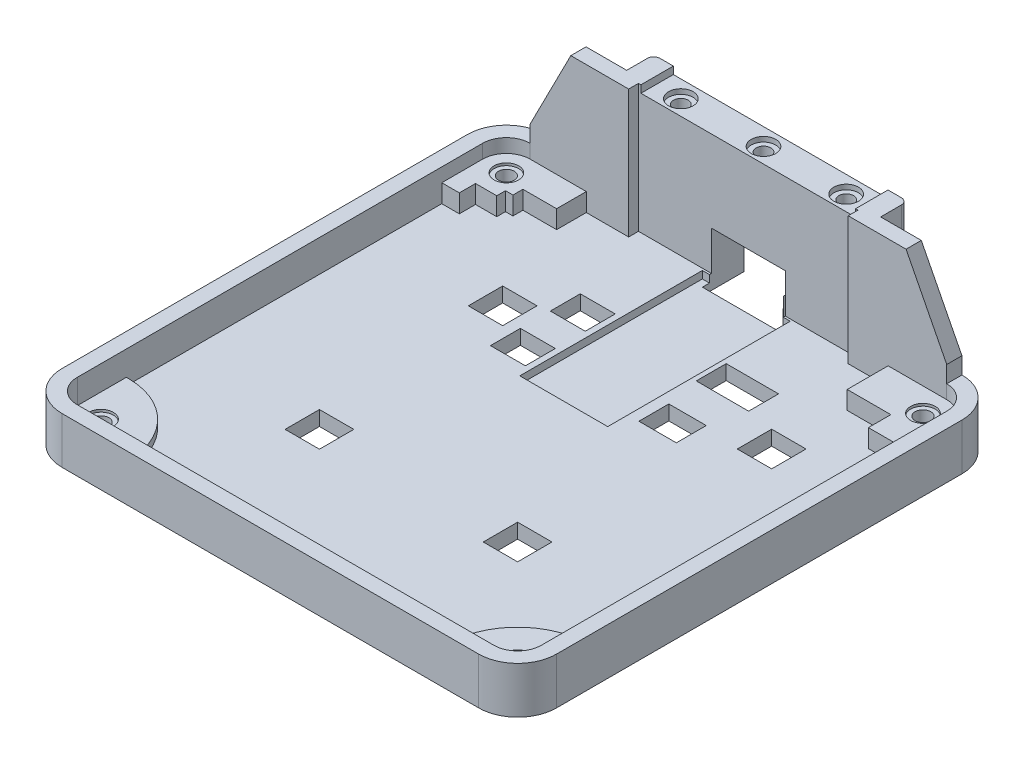
SolidWorks part; units mm, degrees
ref_plane "Front Plane" through (0, 0, 0) normal (0, 0, 1) x (1, 0, 0)
ref_plane "Top Plane" through (0, 0, 0) normal (0, 1, 0) x (1, 0, 0)
ref_plane "Right Plane" through (0, 0, 0) normal (1, 0, 0) x (0, 0, -1)
sketch "Sketch2" plane through (0, 0, 0) normal (0, 1, 0) x (1, 0, 0)
  line L6 (-46.8585, -41.275) -> (-46.8585, 41.275)
  line L8 (46.8585, -41.275) -> (46.8585, 41.275)
  line L9 (42.418, -45.7155) -> (-42.418, -45.7155)
  line L10 (-42.418, 45.7155) -> (-16.8754, 45.7155)
  line L11 (-46.8585, -41.275) -> (-50.3585, -41.275)
  line L14 (-50.3585, -41.275) -> (-50.3585, 41.275)
  line L15 (-42.418, 45.7155) -> (-42.418, 49.2155)
  line L16 (-42.418, 41.275) -> (-37.8452, 38.0373)
  line L17 (-42.418, 49.2155) -> (42.418, 49.2155)
  line L18 (-37.8452, 38.0373) -> (-37.8452, 40.0693)
  line L19 (-37.8452, 40.0693) -> (-30.9872, 40.0693)
  line L20 (-30.9872, 40.0693) -> (-30.9872, 45.7155)
  line L21 (-37.8452, 38.0373) -> (-39.3692, 38.0373)
  line L22 (46.8585, 41.275) -> (50.3585, 41.275)
  line L23 (42.418, -45.7155) -> (42.418, -49.2155)
  line L24 (-39.3692, 38.0373) -> (-39.3692, 36.2593)
  line L25 (42.418, -49.2155) -> (-42.418, -49.2155)
  line L26 (-39.3692, 36.2593) -> (-43.6872, 36.2593)
  line L27 (-43.6872, 36.2593) -> (-43.6872, 32.9573)
  line L28 (50.3585, 41.275) -> (50.3585, -41.275)
  line L34 (-43.6872, 32.9573) -> (-46.8585, 32.9573)
  line L37 (42.418, 41.275) -> (50.0148, 49.9834)
  line L46 (-16.2544, 31.1733) -> (-10.1584, 31.1733)
  line L52 (-10.1584, 31.1733) -> (-10.1584, 25.0773)
  line L58 (-10.1584, 25.0773) -> (-17.2704, 25.0773)
  line L64 (-17.2704, 25.0773) -> (-17.2704, 31.1733)
  line L70 (-17.2704, 31.1733) -> (-16.2544, 31.1733)
  line L76 (-17.2704, 25.0773) -> (-17.2704, 18.9813)
  line L82 (-17.2704, 18.9813) -> (-10.1584, 18.9813)
  line L88 (-10.1584, 18.9813) -> (-10.1584, 12.8853)
  line L94 (-10.1584, 12.8853) -> (-17.2704, 12.8853)
  line L100 (-17.2704, 12.8853) -> (-17.2704, 18.9813)
  line L111 (22.418, 45.7155) -> (42.418, 45.7155)
  line L112 (-10.1584, 31.1733) -> (9.9076, 31.1733)
  line L113 (9.9076, 31.1733) -> (9.9076, 33.7133)
  line L114 (9.9076, 33.7133) -> (20.5756, 33.7133)
  line L115 (20.5756, 33.7133) -> (20.5756, 27.6173)
  line L116 (20.5756, 27.6173) -> (9.9076, 27.6173)
  line L117 (9.9076, 27.6173) -> (9.9076, 31.1733)
  line L118 (9.9076, 27.6173) -> (9.9076, 20.7633)
  line L119 (9.9076, 20.7633) -> (18.7976, 20.7633)
  line L120 (18.7976, 20.7633) -> (18.7976, 14.6673)
  line L121 (18.7976, 14.6673) -> (11.1776, 14.6673)
  line L122 (11.1776, 14.6673) -> (11.1776, 20.7633)
  line L123 (42.418, 41.275) -> (0, 41.275)
  line L124 (42.418, 41.275) -> (39.3704, 37.7815)
  line L125 (39.3704, 37.7815) -> (39.3704, 33.2095)
  line L126 (39.3704, 37.7815) -> (30.4804, 37.7815)
  line L127 (30.4804, 37.7815) -> (30.4804, 45.7155)
  line L128 (39.3704, 33.2095) -> (46.8585, 33.2095)
  line L129 (22.418, 45.7155) -> (-16.8754, 45.7155)
  line L130 (46.8585, -41.275) -> (46.8585, -31.275)
  line L131 (42.418, -45.7155) -> (32.418, -45.7155)
  line L132 (-42.418, -45.7155) -> (-32.418, -45.7155)
  line L133 (-46.8585, -41.275) -> (-46.8585, -31.275)
  arc A0 (-42.418, 45.7155) -> (-46.8585, 41.275) centre (-42.418, 41.275) ccw
  arc A1 (42.418, 45.7155) -> (46.8585, 41.275) centre (42.418, 41.275) cw
  arc A2 (-46.8585, -41.275) -> (-42.418, -45.7155) centre (-42.418, -41.275) ccw
  arc A3 (46.8585, -41.275) -> (42.418, -45.7155) centre (42.418, -41.275) cw
  circle A4 centre (42.418, 41.275) radius 1.6
  circle A5 centre (-42.418, 41.275) radius 1.6
  circle A6 centre (-42.418, -41.275) radius 1.6
  circle A7 centre (42.418, -41.275) radius 1.6
  arc A8 (-42.418, 49.2155) -> (-50.3585, 41.275) centre (-42.418, 41.275) ccw
  arc A9 (42.418, 49.2155) -> (50.3585, 41.275) centre (42.418, 41.275) cw
  arc A10 (42.418, -49.2155) -> (50.3585, -41.275) centre (42.418, -41.275) ccw
  arc A11 (-42.418, -49.2155) -> (-50.3585, -41.275) centre (-42.418, -41.275) cw
  arc A12 (46.8585, -31.275) -> (32.418, -45.7155) centre (46.8585, -45.7155) ccw
  arc A13 (-46.8585, -31.275) -> (-32.418, -45.7155) centre (-46.8585, -45.7155) cw
extrude "Boss-Extrude1" add sketch "Sketch2" along normal blind 1.5 contours L8 A12 L9 A3 A7 | A13 L6 A2 L9 A6 region at (-40.4967, 0, 39.3537) region at (40.4967, 0, 39.3537)
sketch "Sketch5" plane through (0, 0, 0) normal (0, -1, 0) x (1, 0, 0)
  line L0 (-17.2704, -25.0773) -> (-17.2704, -18.9813) construction
  line L1 (42.418, -41.275) -> (50.0148, -49.9834) construction
  line L2 (42.418, -41.275) -> (0, -41.275) construction
  line L3 (42.418, -41.275) -> (39.3704, -37.7815) construction
  line L4 (-42.418, -41.275) -> (-37.8452, -38.0373) construction
  line L5 (-42.418, -45.7155) -> (-16.8754, -45.7155) construction
  line L6 (22.418, -45.7155) -> (-16.8754, -45.7155) construction
  line L7 (22.418, -45.7155) -> (42.418, -45.7155) construction
  line L8 (-42.418, -45.7155) -> (-42.418, -49.2155) construction
  line L9 (-46.8585, 41.275) -> (-46.8585, -41.275) construction
  line L10 (42.418, 45.7155) -> (-42.418, 45.7155) construction
  line L11 (-42.418, 45.7155) -> (-32.418, 45.7155) construction
  line L12 (-46.8585, 41.275) -> (-46.8585, 31.275) construction
  line L13 (42.418, 45.7155) -> (42.418, 49.2155) construction
  line L14 (46.8585, 41.275) -> (46.8585, 31.275) construction
  line L15 (42.418, 45.7155) -> (32.418, 45.7155) construction
  line L16 (46.8585, 41.275) -> (46.8585, -41.275) construction
  line L17 (46.8585, -41.275) -> (50.3585, -41.275) construction
  line L18 (-46.8585, 41.275) -> (-50.3585, 41.275) construction
  line L19 (-37.8452, -38.0373) -> (-39.3692, -38.0373) construction
  line L20 (-39.3692, -38.0373) -> (-39.3692, -36.2593) construction
  line L21 (-39.3692, -36.2593) -> (-43.6872, -36.2593) construction
  line L22 (-43.6872, -36.2593) -> (-43.6872, -32.9573) construction
  line L23 (-43.6872, -32.9573) -> (-46.8585, -32.9573) construction
  line L24 (-37.8452, -38.0373) -> (-37.8452, -40.0693) construction
  line L25 (-37.8452, -40.0693) -> (-30.9872, -40.0693) construction
  line L26 (-30.9872, -40.0693) -> (-30.9872, -45.7155) construction
  line L27 (-42.418, -49.2155) -> (42.418, -49.2155) construction
  line L28 (-50.3585, 41.275) -> (-50.3585, -41.275) construction
  line L29 (42.418, 49.2155) -> (-42.418, 49.2155) construction
  line L30 (9.9076, -31.1733) -> (9.9076, -33.7133) construction
  line L31 (9.9076, -33.7133) -> (20.5756, -33.7133) construction
  line L32 (20.5756, -33.7133) -> (20.5756, -27.6173) construction
  line L33 (20.5756, -27.6173) -> (9.9076, -27.6173) construction
  line L34 (9.9076, -27.6173) -> (9.9076, -31.1733) construction
  line L35 (9.9076, -27.6173) -> (9.9076, -20.7633) construction
  line L36 (9.9076, -20.7633) -> (18.7976, -20.7633) construction
  line L37 (18.7976, -20.7633) -> (18.7976, -14.6673) construction
  line L38 (18.7976, -14.6673) -> (11.1776, -14.6673) construction
  line L39 (11.1776, -14.6673) -> (11.1776, -20.7633) construction
  line L40 (-10.1584, -31.1733) -> (9.9076, -31.1733) construction
  line L41 (50.3585, -41.275) -> (50.3585, 41.275) construction
  line L42 (39.3704, -37.7815) -> (39.3704, -33.2095) construction
  line L43 (39.3704, -33.2095) -> (46.8585, -33.2095) construction
  line L44 (39.3704, -37.7815) -> (30.4804, -37.7815) construction
  line L45 (30.4804, -37.7815) -> (30.4804, -45.7155) construction
  line L46 (-10.1584, -31.1733) -> (-10.1584, -25.0773) construction
  line L47 (-10.1584, -25.0773) -> (-17.2704, -25.0773) construction
  line L48 (-16.2544, -31.1733) -> (-10.1584, -31.1733) construction
  line L49 (-17.2704, -31.1733) -> (-16.2544, -31.1733) construction
  line L50 (-17.2704, -25.0773) -> (-17.2704, -31.1733) construction
  line L51 (-17.2704, -18.9813) -> (-10.1584, -18.9813) construction
  line L52 (-10.1584, -18.9813) -> (-10.1584, -12.8853) construction
  line L53 (-10.1584, -12.8853) -> (-17.2704, -12.8853) construction
  line L54 (-17.2704, -12.8853) -> (-17.2704, -18.9813) construction
  line L55 (-17.2704, -25.0773) -> (-17.2704, -18.9813)
  line L56 (42.418, -41.275) -> (50.0148, -49.9834)
  line L57 (42.418, -41.275) -> (0, -41.275)
  line L58 (42.418, -41.275) -> (39.3704, -37.7815)
  line L59 (-42.418, -41.275) -> (-37.8452, -38.0373)
  line L60 (-42.418, -45.7155) -> (-16.8754, -45.7155)
  line L61 (22.418, -45.7155) -> (-16.8754, -45.7155)
  line L62 (22.418, -45.7155) -> (42.418, -45.7155)
  line L63 (-42.418, -45.7155) -> (-42.418, -49.2155)
  line L64 (-46.8585, 41.275) -> (-46.8585, -41.275)
  line L65 (42.418, 45.7155) -> (-42.418, 45.7155)
  line L66 (-42.418, 45.7155) -> (-32.418, 45.7155)
  line L67 (-46.8585, 41.275) -> (-46.8585, 31.275)
  line L68 (42.418, 45.7155) -> (42.418, 49.2155)
  line L69 (46.8585, 41.275) -> (46.8585, 31.275)
  line L70 (42.418, 45.7155) -> (32.418, 45.7155)
  line L71 (46.8585, 41.275) -> (46.8585, -41.275)
  line L72 (46.8585, -41.275) -> (50.3585, -41.275)
  line L73 (-46.8585, 41.275) -> (-50.3585, 41.275)
  line L74 (-37.8452, -38.0373) -> (-39.3692, -38.0373)
  line L75 (-39.3692, -38.0373) -> (-39.3692, -36.2593)
  line L76 (-39.3692, -36.2593) -> (-43.6872, -36.2593)
  line L77 (-43.6872, -36.2593) -> (-43.6872, -32.9573)
  line L78 (-43.6872, -32.9573) -> (-46.8585, -32.9573)
  line L79 (-37.8452, -38.0373) -> (-37.8452, -40.0693)
  line L80 (-37.8452, -40.0693) -> (-30.9872, -40.0693)
  line L81 (-30.9872, -40.0693) -> (-30.9872, -45.7155)
  line L82 (-42.418, -49.2155) -> (42.418, -49.2155)
  line L83 (-50.3585, 41.275) -> (-50.3585, -41.275)
  line L84 (42.418, 49.2155) -> (-42.418, 49.2155)
  line L85 (9.9076, -31.1733) -> (9.9076, -33.7133)
  line L86 (9.9076, -33.7133) -> (20.5756, -33.7133)
  line L87 (20.5756, -33.7133) -> (20.5756, -27.6173)
  line L88 (20.5756, -27.6173) -> (9.9076, -27.6173)
  line L89 (9.9076, -27.6173) -> (9.9076, -31.1733)
  line L90 (9.9076, -27.6173) -> (9.9076, -20.7633)
  line L91 (9.9076, -20.7633) -> (18.7976, -20.7633)
  line L92 (18.7976, -20.7633) -> (18.7976, -14.6673)
  line L93 (18.7976, -14.6673) -> (11.1776, -14.6673)
  line L94 (11.1776, -14.6673) -> (11.1776, -20.7633)
  line L95 (-10.1584, -31.1733) -> (9.9076, -31.1733)
  line L96 (50.3585, -41.275) -> (50.3585, 41.275)
  line L97 (39.3704, -37.7815) -> (39.3704, -33.2095)
  line L98 (39.3704, -33.2095) -> (46.8585, -33.2095)
  line L99 (39.3704, -37.7815) -> (30.4804, -37.7815)
  line L100 (30.4804, -37.7815) -> (30.4804, -45.7155)
  line L101 (-10.1584, -31.1733) -> (-10.1584, -25.0773)
  line L102 (-10.1584, -25.0773) -> (-17.2704, -25.0773)
  line L103 (-16.2544, -31.1733) -> (-10.1584, -31.1733)
  line L104 (-17.2704, -31.1733) -> (-16.2544, -31.1733)
  line L105 (-17.2704, -25.0773) -> (-17.2704, -31.1733)
  line L106 (-17.2704, -18.9813) -> (-10.1584, -18.9813)
  line L107 (-10.1584, -18.9813) -> (-10.1584, -12.8853)
  line L108 (-10.1584, -12.8853) -> (-17.2704, -12.8853)
  line L109 (-17.2704, -12.8853) -> (-17.2704, -18.9813)
  line L110 (50.3585, -41.275) -> (50.3585, 41.275)
  line L111 (42.418, 49.2155) -> (-42.418, 49.2155)
  line L112 (-50.3585, 41.275) -> (-50.3585, -41.275)
  line L113 (-42.418, -49.2155) -> (42.418, -49.2155)
  arc A0 (42.418, -45.7155) -> (46.8585, -41.275) centre (42.418, -41.275) ccw construction
  arc A1 (-46.8585, -41.275) -> (-42.418, -45.7155) centre (-42.418, -41.275) ccw construction
  arc A2 (-46.8585, 31.275) -> (-32.418, 45.7155) centre (-46.8585, 45.7155) ccw construction
  arc A3 (-42.418, 45.7155) -> (-46.8585, 41.275) centre (-42.418, 41.275) ccw construction
  arc A4 (32.418, 45.7155) -> (46.8585, 31.275) centre (46.8585, 45.7155) ccw construction
  arc A5 (46.8585, 41.275) -> (42.418, 45.7155) centre (42.418, 41.275) ccw construction
  arc A6 (42.418, -49.2155) -> (50.3585, -41.275) centre (42.418, -41.275) ccw construction
  arc A7 (-50.3585, -41.275) -> (-42.418, -49.2155) centre (-42.418, -41.275) ccw construction
  arc A8 (-42.418, 49.2155) -> (-50.3585, 41.275) centre (-42.418, 41.275) ccw construction
  arc A9 (50.3585, 41.275) -> (42.418, 49.2155) centre (42.418, 41.275) ccw construction
  circle A10 centre (42.418, 41.275) radius 1.6 construction
  circle A11 centre (-42.418, 41.275) radius 1.6 construction
  circle A12 centre (-42.418, -41.275) radius 1.6 construction
  circle A13 centre (42.418, -41.275) radius 1.6 construction
  arc A14 (42.418, -45.7155) -> (46.8585, -41.275) centre (42.418, -41.275) ccw
  arc A15 (-46.8585, -41.275) -> (-42.418, -45.7155) centre (-42.418, -41.275) ccw
  arc A16 (-46.8585, 31.275) -> (-32.418, 45.7155) centre (-46.8585, 45.7155) ccw
  arc A17 (-42.418, 45.7155) -> (-46.8585, 41.275) centre (-42.418, 41.275) ccw
  arc A18 (32.418, 45.7155) -> (46.8585, 31.275) centre (46.8585, 45.7155) ccw
  arc A19 (46.8585, 41.275) -> (42.418, 45.7155) centre (42.418, 41.275) ccw
  arc A20 (42.418, -49.2155) -> (50.3585, -41.275) centre (42.418, -41.275) ccw
  arc A21 (-50.3585, -41.275) -> (-42.418, -49.2155) centre (-42.418, -41.275) ccw
  arc A22 (-42.418, 49.2155) -> (-50.3585, 41.275) centre (-42.418, 41.275) ccw
  arc A23 (50.3585, 41.275) -> (42.418, 49.2155) centre (42.418, 41.275) ccw
  circle A24 centre (42.418, 41.275) radius 1.6
  circle A25 centre (-42.418, 41.275) radius 1.6
  circle A26 centre (-42.418, -41.275) radius 1.6
  circle A27 centre (42.418, -41.275) radius 1.6
  arc A28 (42.418, -49.2155) -> (50.3585, -41.275) centre (42.418, -41.275) ccw
  arc A29 (50.3585, 41.275) -> (42.418, 49.2155) centre (42.418, 41.275) ccw
  arc A30 (-42.418, 49.2155) -> (-50.3585, 41.275) centre (-42.418, 41.275) ccw
  arc A31 (-50.3585, -41.275) -> (-42.418, -49.2155) centre (-42.418, -41.275) ccw
  arc M1 (-46.8585, 31.275) -> (-32.418, 45.7155) centre (-46.8585, 45.7155) ccw
  line M2 (-32.418, 45.7155) -> (-42.418, 45.7155)
  arc M3 (-42.418, 45.7155) -> (-46.8585, 41.275) centre (-42.418, 41.275) ccw
  line M4 (-46.8585, 41.275) -> (-46.8585, 31.275)
  circle M5 centre (-42.418, 41.275) radius 1.6
extrude "Boss-Extrude3" add sketch "Sketch5" along normal blind 2 contours L82 A20 L56 A14 L62 L61 L60 L63 | L56 A20 L72 A14 | L96 A23 L68 A19 L69 L71 L72 | A18 L65 L64 L78 L77 L76 L75 L74 L79 L80 L81 L60 L61 L62 L100 L99 L97 L98 L71 L109 L108 L107 L106 L102 L101 L89 L94 L93 L92 L91 L88 L87 L86 L85 L103 L104 L105 M1 | A27 L58 L99 L100 L57 | A27 L57 L100 L62 A14 L56 | A27 L56 A14 L71 L98 L97 L58 | A26 L74 L75 L76 L77 L78 L64 A15 L60 L81 L80 L79 | M4 M1 M2 M3 M5 | L69 A19 L65 A18 A24 | L84 A22 L73 L65 L68 M3 M2 | L83 A21 L63 A15 L64 L73 M4 region at (43.6425, 0, -37.4818) region at (37.0258, 0, -43.6304) region at (35.5464, 0, -39.5753) region at (48.0295, 0, -43.8264) region at (2.2185, 0, -47.4473) region at (-0.2178, 0, 0.4927) region at (48.3825, 0, 4.776) region at (-48.3825, 0, -4.776) region at (40.4967, 0, 39.3537) region at (-39.9913, 0, -40.9811) region at (-4.7781, 0, 47.245) region at (-40.4967, 0, 39.3537)
sketch "Sketch6" plane through (0, 0, 0) normal (0, 1, 0) x (1, 0, 0)
  line L0 (-17.2704, 25.0773) -> (-17.2704, 18.9813) construction
  line L1 (42.418, 41.275) -> (50.0148, 49.9834) construction
  line L2 (42.418, 41.275) -> (0, 41.275) construction
  line L3 (42.418, 41.275) -> (39.3704, 37.7815) construction
  line L4 (-42.418, 41.275) -> (-37.8452, 38.0373) construction
  line L5 (-42.418, 45.7155) -> (-16.8754, 45.7155) construction
  line L6 (22.418, 45.7155) -> (-16.8754, 45.7155) construction
  line L7 (22.418, 45.7155) -> (42.418, 45.7155) construction
  line L8 (-42.418, 45.7155) -> (-42.418, 49.2155) construction
  line L9 (-46.8585, -41.275) -> (-46.8585, 41.275) construction
  line L10 (42.418, -45.7155) -> (-42.418, -45.7155) construction
  line L11 (-42.418, -45.7155) -> (-32.418, -45.7155) construction
  line L12 (-46.8585, -41.275) -> (-46.8585, -31.275) construction
  line L13 (42.418, -45.7155) -> (42.418, -49.2155) construction
  line L14 (46.8585, -41.275) -> (46.8585, -31.275) construction
  line L15 (42.418, -45.7155) -> (32.418, -45.7155) construction
  line L16 (46.8585, -41.275) -> (46.8585, 41.275) construction
  line L17 (46.8585, 41.275) -> (50.3585, 41.275) construction
  line L18 (-46.8585, -41.275) -> (-50.3585, -41.275) construction
  line L19 (-37.8452, 38.0373) -> (-39.3692, 38.0373) construction
  line L20 (-39.3692, 38.0373) -> (-39.3692, 36.2593) construction
  line L21 (-39.3692, 36.2593) -> (-43.6872, 36.2593) construction
  line L22 (-43.6872, 36.2593) -> (-43.6872, 32.9573) construction
  line L23 (-43.6872, 32.9573) -> (-46.8585, 32.9573) construction
  line L24 (-37.8452, 38.0373) -> (-37.8452, 40.0693) construction
  line L25 (-37.8452, 40.0693) -> (-30.9872, 40.0693) construction
  line L26 (-30.9872, 40.0693) -> (-30.9872, 45.7155) construction
  line L27 (-42.418, 49.2155) -> (42.418, 49.2155) construction
  line L28 (-50.3585, -41.275) -> (-50.3585, 41.275) construction
  line L29 (42.418, -49.2155) -> (-42.418, -49.2155) construction
  line L30 (9.9076, 31.1733) -> (9.9076, 33.7133) construction
  line L31 (9.9076, 33.7133) -> (20.5756, 33.7133) construction
  line L32 (20.5756, 33.7133) -> (20.5756, 27.6173) construction
  line L33 (20.5756, 27.6173) -> (9.9076, 27.6173) construction
  line L34 (9.9076, 27.6173) -> (9.9076, 31.1733) construction
  line L35 (9.9076, 27.6173) -> (9.9076, 20.7633) construction
  line L36 (9.9076, 20.7633) -> (18.7976, 20.7633) construction
  line L37 (18.7976, 20.7633) -> (18.7976, 14.6673) construction
  line L38 (18.7976, 14.6673) -> (11.1776, 14.6673) construction
  line L39 (11.1776, 14.6673) -> (11.1776, 20.7633) construction
  line L40 (-10.1584, 31.1733) -> (9.9076, 31.1733) construction
  line L41 (50.3585, 41.275) -> (50.3585, -41.275) construction
  line L42 (39.3704, 37.7815) -> (39.3704, 33.2095) construction
  line L43 (39.3704, 33.2095) -> (46.8585, 33.2095) construction
  line L44 (39.3704, 37.7815) -> (30.4804, 37.7815) construction
  line L45 (30.4804, 37.7815) -> (30.4804, 45.7155) construction
  line L46 (-10.1584, 31.1733) -> (-10.1584, 25.0773) construction
  line L47 (-10.1584, 25.0773) -> (-17.2704, 25.0773) construction
  line L48 (-16.2544, 31.1733) -> (-10.1584, 31.1733) construction
  line L49 (-17.2704, 31.1733) -> (-16.2544, 31.1733) construction
  line L50 (-17.2704, 25.0773) -> (-17.2704, 31.1733) construction
  line L51 (-17.2704, 18.9813) -> (-10.1584, 18.9813) construction
  line L52 (-10.1584, 18.9813) -> (-10.1584, 12.8853) construction
  line L53 (-10.1584, 12.8853) -> (-17.2704, 12.8853) construction
  line L54 (-17.2704, 12.8853) -> (-17.2704, 18.9813) construction
  line L55 (-17.2704, 25.0773) -> (-17.2704, 18.9813)
  line L56 (42.418, 41.275) -> (50.0148, 49.9834)
  line L57 (42.418, 41.275) -> (0, 41.275)
  line L58 (42.418, 41.275) -> (39.3704, 37.7815)
  line L59 (-42.418, 41.275) -> (-37.8452, 38.0373)
  line L60 (-42.418, 45.7155) -> (-16.8754, 45.7155)
  line L61 (22.418, 45.7155) -> (-16.8754, 45.7155)
  line L62 (22.418, 45.7155) -> (42.418, 45.7155)
  line L63 (-42.418, 45.7155) -> (-42.418, 49.2155)
  line L64 (-46.8585, -41.275) -> (-46.8585, 41.275)
  line L65 (42.418, -45.7155) -> (-42.418, -45.7155)
  line L66 (-42.418, -45.7155) -> (-32.418, -45.7155)
  line L67 (-46.8585, -41.275) -> (-46.8585, -31.275)
  line L68 (42.418, -45.7155) -> (42.418, -49.2155)
  line L69 (46.8585, -41.275) -> (46.8585, -31.275)
  line L70 (42.418, -45.7155) -> (32.418, -45.7155)
  line L71 (46.8585, -41.275) -> (46.8585, 41.275)
  line L72 (46.8585, 41.275) -> (50.3585, 41.275)
  line L73 (-46.8585, -41.275) -> (-50.3585, -41.275)
  line L74 (-37.8452, 38.0373) -> (-39.3692, 38.0373)
  line L75 (-39.3692, 38.0373) -> (-39.3692, 36.2593)
  line L76 (-39.3692, 36.2593) -> (-43.6872, 36.2593)
  line L77 (-43.6872, 36.2593) -> (-43.6872, 32.9573)
  line L78 (-43.6872, 32.9573) -> (-46.8585, 32.9573)
  line L79 (-37.8452, 38.0373) -> (-37.8452, 40.0693)
  line L80 (-37.8452, 40.0693) -> (-30.9872, 40.0693)
  line L81 (-30.9872, 40.0693) -> (-30.9872, 45.7155)
  line L82 (-42.418, 49.2155) -> (42.418, 49.2155)
  line L83 (-50.3585, -41.275) -> (-50.3585, 41.275)
  line L84 (42.418, -49.2155) -> (-42.418, -49.2155)
  line L85 (9.9076, 31.1733) -> (9.9076, 33.7133)
  line L86 (9.9076, 33.7133) -> (20.5756, 33.7133)
  line L87 (20.5756, 33.7133) -> (20.5756, 27.6173)
  line L88 (20.5756, 27.6173) -> (9.9076, 27.6173)
  line L89 (9.9076, 27.6173) -> (9.9076, 31.1733)
  line L90 (9.9076, 27.6173) -> (9.9076, 20.7633)
  line L91 (9.9076, 20.7633) -> (18.7976, 20.7633)
  line L92 (18.7976, 20.7633) -> (18.7976, 14.6673)
  line L93 (18.7976, 14.6673) -> (11.1776, 14.6673)
  line L94 (11.1776, 14.6673) -> (11.1776, 20.7633)
  line L95 (-10.1584, 31.1733) -> (9.9076, 31.1733)
  line L96 (50.3585, 41.275) -> (50.3585, -41.275)
  line L97 (39.3704, 37.7815) -> (39.3704, 33.2095)
  line L98 (39.3704, 33.2095) -> (46.8585, 33.2095)
  line L99 (39.3704, 37.7815) -> (30.4804, 37.7815)
  line L100 (30.4804, 37.7815) -> (30.4804, 45.7155)
  line L101 (-10.1584, 31.1733) -> (-10.1584, 25.0773)
  line L102 (-10.1584, 25.0773) -> (-17.2704, 25.0773)
  line L103 (-16.2544, 31.1733) -> (-10.1584, 31.1733)
  line L104 (-17.2704, 31.1733) -> (-16.2544, 31.1733)
  line L105 (-17.2704, 25.0773) -> (-17.2704, 31.1733)
  line L106 (-17.2704, 18.9813) -> (-10.1584, 18.9813)
  line L107 (-10.1584, 18.9813) -> (-10.1584, 12.8853)
  line L108 (-10.1584, 12.8853) -> (-17.2704, 12.8853)
  line L109 (-17.2704, 12.8853) -> (-17.2704, 18.9813)
  line L110 (30.4804, 45.7155) -> (30.4804, 37.7815)
  line L111 (39.3704, 37.7815) -> (39.3704, 33.2095)
  line L112 (30.4804, 37.7815) -> (39.3704, 37.7815)
  line L113 (39.3704, 33.2095) -> (46.8585, 33.2095)
  line L114 (46.8585, 33.2095) -> (46.8585, 41.275)
  line L115 (42.418, 45.7155) -> (30.4804, 45.7155)
  line L116 (-42.418, 45.7155) -> (-30.9872, 45.7155)
  line L117 (-30.9872, 45.7155) -> (-30.9872, 40.0693)
  line L118 (-30.9872, 40.0693) -> (-37.8452, 40.0693)
  line L119 (-37.8452, 40.0693) -> (-37.8452, 38.0373)
  line L120 (-37.8452, 38.0373) -> (-39.3692, 38.0373)
  line L121 (-39.3692, 38.0373) -> (-39.3692, 36.2593)
  line L122 (-39.3692, 36.2593) -> (-43.6872, 36.2593)
  line L123 (-43.6872, 36.2593) -> (-43.6872, 32.9573)
  line L124 (-43.6872, 32.9573) -> (-46.8585, 32.9573)
  line L125 (-46.8585, 32.9573) -> (-46.8585, 41.275)
  arc A0 (46.8585, 41.275) -> (42.418, 45.7155) centre (42.418, 41.275) ccw construction
  arc A1 (-42.418, 45.7155) -> (-46.8585, 41.275) centre (-42.418, 41.275) ccw construction
  arc A2 (-32.418, -45.7155) -> (-46.8585, -31.275) centre (-46.8585, -45.7155) ccw construction
  arc A3 (-46.8585, -41.275) -> (-42.418, -45.7155) centre (-42.418, -41.275) ccw construction
  arc A4 (46.8585, -31.275) -> (32.418, -45.7155) centre (46.8585, -45.7155) ccw construction
  arc A5 (42.418, -45.7155) -> (46.8585, -41.275) centre (42.418, -41.275) ccw construction
  arc A6 (50.3585, 41.275) -> (42.418, 49.2155) centre (42.418, 41.275) ccw construction
  arc A7 (-42.418, 49.2155) -> (-50.3585, 41.275) centre (-42.418, 41.275) ccw construction
  arc A8 (-50.3585, -41.275) -> (-42.418, -49.2155) centre (-42.418, -41.275) ccw construction
  arc A9 (42.418, -49.2155) -> (50.3585, -41.275) centre (42.418, -41.275) ccw construction
  circle A10 centre (42.418, -41.275) radius 1.6 construction
  circle A11 centre (-42.418, -41.275) radius 1.6 construction
  circle A12 centre (-42.418, 41.275) radius 1.6 construction
  circle A13 centre (42.418, 41.275) radius 1.6 construction
  arc A14 (46.8585, 41.275) -> (42.418, 45.7155) centre (42.418, 41.275) ccw
  arc A15 (-42.418, 45.7155) -> (-46.8585, 41.275) centre (-42.418, 41.275) ccw
  arc A16 (-32.418, -45.7155) -> (-46.8585, -31.275) centre (-46.8585, -45.7155) ccw
  arc A17 (-46.8585, -41.275) -> (-42.418, -45.7155) centre (-42.418, -41.275) ccw
  arc A18 (46.8585, -31.275) -> (32.418, -45.7155) centre (46.8585, -45.7155) ccw
  arc A19 (42.418, -45.7155) -> (46.8585, -41.275) centre (42.418, -41.275) ccw
  arc A20 (50.3585, 41.275) -> (42.418, 49.2155) centre (42.418, 41.275) ccw
  arc A21 (-42.418, 49.2155) -> (-50.3585, 41.275) centre (-42.418, 41.275) ccw
  arc A22 (-50.3585, -41.275) -> (-42.418, -49.2155) centre (-42.418, -41.275) ccw
  arc A23 (42.418, -49.2155) -> (50.3585, -41.275) centre (42.418, -41.275) ccw
  circle A24 centre (42.418, -41.275) radius 1.6
  circle A25 centre (-42.418, -41.275) radius 1.6
  circle A26 centre (-42.418, 41.275) radius 1.6
  circle A27 centre (42.418, 41.275) radius 1.6
  arc A28 (-46.8585, 41.275) -> (-42.418, 45.7155) centre (-42.418, 41.275) cw
  arc A29 (46.8585, 41.275) -> (42.418, 45.7155) centre (42.418, 41.275) ccw
  circle M17 centre (42.418, 41.275) radius 1.6
  circle M34 centre (-42.418, 41.275) radius 1.6
extrude "Boss-Extrude4" add sketch "Sketch6" along normal blind 3.7 contours L56 A14 L62 L100 L57 M17 | L100 L99 L58 L57 M17 | L71 A14 L56 L58 L97 L98 M17 | L60 A15 L64 L78 L77 L76 L75 L74 L79 L80 L81 M34 region at (37.0258, 0, -43.6304) region at (43.6425, 0, -37.4818) region at (35.5464, 0, -39.5753) region at (-39.9913, 0, -40.9811)
sketch "Sketch7" plane through (0, 0, 0) normal (0, 1, 0) x (1, 0, 0)
  line L0 (-17.2704, 25.0773) -> (-17.2704, 18.9813) construction
  line L1 (42.418, 41.275) -> (50.0148, 49.9834) construction
  line L2 (42.418, 41.275) -> (0, 41.275) construction
  line L3 (42.418, 41.275) -> (39.3704, 37.7815) construction
  line L4 (-42.418, 41.275) -> (-37.8452, 38.0373) construction
  line L5 (-42.418, 45.7155) -> (-16.8754, 45.7155) construction
  line L6 (22.418, 45.7155) -> (-16.8754, 45.7155) construction
  line L7 (22.418, 45.7155) -> (42.418, 45.7155) construction
  line L8 (-42.418, 45.7155) -> (-42.418, 49.2155) construction
  line L9 (-46.8585, -41.275) -> (-46.8585, 41.275) construction
  line L10 (42.418, -45.7155) -> (-42.418, -45.7155) construction
  line L11 (-42.418, -45.7155) -> (-32.418, -45.7155) construction
  line L12 (-46.8585, -41.275) -> (-46.8585, -31.275) construction
  line L13 (42.418, -45.7155) -> (42.418, -49.2155) construction
  line L14 (46.8585, -41.275) -> (46.8585, -31.275) construction
  line L15 (42.418, -45.7155) -> (32.418, -45.7155) construction
  line L16 (46.8585, -41.275) -> (46.8585, 41.275) construction
  line L17 (46.8585, 41.275) -> (50.3585, 41.275) construction
  line L18 (-46.8585, -41.275) -> (-50.3585, -41.275) construction
  line L19 (-37.8452, 38.0373) -> (-39.3692, 38.0373) construction
  line L20 (-39.3692, 38.0373) -> (-39.3692, 36.2593) construction
  line L21 (-39.3692, 36.2593) -> (-43.6872, 36.2593) construction
  line L22 (-43.6872, 36.2593) -> (-43.6872, 32.9573) construction
  line L23 (-43.6872, 32.9573) -> (-46.8585, 32.9573) construction
  line L24 (-37.8452, 38.0373) -> (-37.8452, 40.0693) construction
  line L25 (-37.8452, 40.0693) -> (-30.9872, 40.0693) construction
  line L26 (-30.9872, 40.0693) -> (-30.9872, 45.7155) construction
  line L27 (-42.418, 49.2155) -> (42.418, 49.2155) construction
  line L28 (-50.3585, -41.275) -> (-50.3585, 41.275) construction
  line L29 (42.418, -49.2155) -> (-42.418, -49.2155) construction
  line L30 (9.9076, 31.1733) -> (9.9076, 33.7133) construction
  line L31 (9.9076, 33.7133) -> (20.5756, 33.7133) construction
  line L32 (20.5756, 33.7133) -> (20.5756, 27.6173) construction
  line L33 (20.5756, 27.6173) -> (9.9076, 27.6173) construction
  line L34 (9.9076, 27.6173) -> (9.9076, 31.1733) construction
  line L35 (9.9076, 27.6173) -> (9.9076, 20.7633) construction
  line L36 (9.9076, 20.7633) -> (18.7976, 20.7633) construction
  line L37 (18.7976, 20.7633) -> (18.7976, 14.6673) construction
  line L38 (18.7976, 14.6673) -> (11.1776, 14.6673) construction
  line L39 (11.1776, 14.6673) -> (11.1776, 20.7633) construction
  line L40 (-10.1584, 31.1733) -> (9.9076, 31.1733) construction
  line L41 (50.3585, 41.275) -> (50.3585, -41.275) construction
  line L42 (39.3704, 37.7815) -> (39.3704, 33.2095) construction
  line L43 (39.3704, 33.2095) -> (46.8585, 33.2095) construction
  line L44 (39.3704, 37.7815) -> (30.4804, 37.7815) construction
  line L45 (30.4804, 37.7815) -> (30.4804, 45.7155) construction
  line L46 (-10.1584, 31.1733) -> (-10.1584, 25.0773) construction
  line L47 (-10.1584, 25.0773) -> (-17.2704, 25.0773) construction
  line L48 (-16.2544, 31.1733) -> (-10.1584, 31.1733) construction
  line L49 (-17.2704, 31.1733) -> (-16.2544, 31.1733) construction
  line L50 (-17.2704, 25.0773) -> (-17.2704, 31.1733) construction
  line L51 (-17.2704, 18.9813) -> (-10.1584, 18.9813) construction
  line L52 (-10.1584, 18.9813) -> (-10.1584, 12.8853) construction
  line L53 (-10.1584, 12.8853) -> (-17.2704, 12.8853) construction
  line L54 (-17.2704, 12.8853) -> (-17.2704, 18.9813) construction
  line L55 (-17.2704, 25.0773) -> (-17.2704, 18.9813)
  line L56 (42.418, 41.275) -> (50.0148, 49.9834)
  line L57 (42.418, 41.275) -> (0, 41.275)
  line L58 (42.418, 41.275) -> (39.3704, 37.7815)
  line L59 (-42.418, 41.275) -> (-37.8452, 38.0373)
  line L60 (-42.418, 45.7155) -> (-16.8754, 45.7155)
  line L61 (22.418, 45.7155) -> (-16.8754, 45.7155)
  line L62 (22.418, 45.7155) -> (42.418, 45.7155)
  line L63 (-42.418, 45.7155) -> (-42.418, 49.2155)
  line L64 (-46.8585, -41.275) -> (-46.8585, 41.275)
  line L65 (42.418, -45.7155) -> (-42.418, -45.7155)
  line L66 (-42.418, -45.7155) -> (-32.418, -45.7155)
  line L67 (-46.8585, -41.275) -> (-46.8585, -31.275)
  line L68 (42.418, -45.7155) -> (42.418, -49.2155)
  line L69 (46.8585, -41.275) -> (46.8585, -31.275)
  line L70 (42.418, -45.7155) -> (32.418, -45.7155)
  line L71 (46.8585, -41.275) -> (46.8585, 41.275)
  line L72 (46.8585, 41.275) -> (50.3585, 41.275)
  line L73 (-46.8585, -41.275) -> (-50.3585, -41.275)
  line L74 (-37.8452, 38.0373) -> (-39.3692, 38.0373)
  line L75 (-39.3692, 38.0373) -> (-39.3692, 36.2593)
  line L76 (-39.3692, 36.2593) -> (-43.6872, 36.2593)
  line L77 (-43.6872, 36.2593) -> (-43.6872, 32.9573)
  line L78 (-43.6872, 32.9573) -> (-46.8585, 32.9573)
  line L79 (-37.8452, 38.0373) -> (-37.8452, 40.0693)
  line L80 (-37.8452, 40.0693) -> (-30.9872, 40.0693)
  line L81 (-30.9872, 40.0693) -> (-30.9872, 45.7155)
  line L82 (-42.418, 49.2155) -> (42.418, 49.2155)
  line L83 (-50.3585, -41.275) -> (-50.3585, 41.275)
  line L84 (42.418, -49.2155) -> (-42.418, -49.2155)
  line L85 (9.9076, 31.1733) -> (9.9076, 33.7133)
  line L86 (9.9076, 33.7133) -> (20.5756, 33.7133)
  line L87 (20.5756, 33.7133) -> (20.5756, 27.6173)
  line L88 (20.5756, 27.6173) -> (9.9076, 27.6173)
  line L89 (9.9076, 27.6173) -> (9.9076, 31.1733)
  line L90 (9.9076, 27.6173) -> (9.9076, 20.7633)
  line L91 (9.9076, 20.7633) -> (18.7976, 20.7633)
  line L92 (18.7976, 20.7633) -> (18.7976, 14.6673)
  line L93 (18.7976, 14.6673) -> (11.1776, 14.6673)
  line L94 (11.1776, 14.6673) -> (11.1776, 20.7633)
  line L95 (-10.1584, 31.1733) -> (9.9076, 31.1733)
  line L96 (50.3585, 41.275) -> (50.3585, -41.275)
  line L97 (39.3704, 37.7815) -> (39.3704, 33.2095)
  line L98 (39.3704, 33.2095) -> (46.8585, 33.2095)
  line L99 (39.3704, 37.7815) -> (30.4804, 37.7815)
  line L100 (30.4804, 37.7815) -> (30.4804, 45.7155)
  line L101 (-10.1584, 31.1733) -> (-10.1584, 25.0773)
  line L102 (-10.1584, 25.0773) -> (-17.2704, 25.0773)
  line L103 (-16.2544, 31.1733) -> (-10.1584, 31.1733)
  line L104 (-17.2704, 31.1733) -> (-16.2544, 31.1733)
  line L105 (-17.2704, 25.0773) -> (-17.2704, 31.1733)
  line L106 (-17.2704, 18.9813) -> (-10.1584, 18.9813)
  line L107 (-10.1584, 18.9813) -> (-10.1584, 12.8853)
  line L108 (-10.1584, 12.8853) -> (-17.2704, 12.8853)
  line L109 (-17.2704, 12.8853) -> (-17.2704, 18.9813)
  line L110 (0, 41.275) -> (-7.5, 41.275)
  line L111 (0, 41.275) -> (7.5, 41.275)
  line L112 (7.5, 41.275) -> (7.5, 49.2155)
  line L113 (-7.5, 41.275) -> (-7.5, 49.2155)
  arc A0 (46.8585, 41.275) -> (42.418, 45.7155) centre (42.418, 41.275) ccw construction
  arc A1 (-42.418, 45.7155) -> (-46.8585, 41.275) centre (-42.418, 41.275) ccw construction
  arc A2 (-32.418, -45.7155) -> (-46.8585, -31.275) centre (-46.8585, -45.7155) ccw construction
  arc A3 (-46.8585, -41.275) -> (-42.418, -45.7155) centre (-42.418, -41.275) ccw construction
  arc A4 (46.8585, -31.275) -> (32.418, -45.7155) centre (46.8585, -45.7155) ccw construction
  arc A5 (42.418, -45.7155) -> (46.8585, -41.275) centre (42.418, -41.275) ccw construction
  arc A6 (50.3585, 41.275) -> (42.418, 49.2155) centre (42.418, 41.275) ccw construction
  arc A7 (-42.418, 49.2155) -> (-50.3585, 41.275) centre (-42.418, 41.275) ccw construction
  arc A8 (-50.3585, -41.275) -> (-42.418, -49.2155) centre (-42.418, -41.275) ccw construction
  arc A9 (42.418, -49.2155) -> (50.3585, -41.275) centre (42.418, -41.275) ccw construction
  circle A10 centre (42.418, -41.275) radius 1.6 construction
  circle A11 centre (-42.418, -41.275) radius 1.6 construction
  circle A12 centre (-42.418, 41.275) radius 1.6 construction
  circle A13 centre (42.418, 41.275) radius 1.6 construction
  arc A14 (46.8585, 41.275) -> (42.418, 45.7155) centre (42.418, 41.275) ccw
  arc A15 (-42.418, 45.7155) -> (-46.8585, 41.275) centre (-42.418, 41.275) ccw
  arc A16 (-32.418, -45.7155) -> (-46.8585, -31.275) centre (-46.8585, -45.7155) ccw
  arc A17 (-46.8585, -41.275) -> (-42.418, -45.7155) centre (-42.418, -41.275) ccw
  arc A18 (46.8585, -31.275) -> (32.418, -45.7155) centre (46.8585, -45.7155) ccw
  arc A19 (42.418, -45.7155) -> (46.8585, -41.275) centre (42.418, -41.275) ccw
  arc A20 (50.3585, 41.275) -> (42.418, 49.2155) centre (42.418, 41.275) ccw
  arc A21 (-42.418, 49.2155) -> (-50.3585, 41.275) centre (-42.418, 41.275) ccw
  arc A22 (-50.3585, -41.275) -> (-42.418, -49.2155) centre (-42.418, -41.275) ccw
  arc A23 (42.418, -49.2155) -> (50.3585, -41.275) centre (42.418, -41.275) ccw
  circle A24 centre (42.418, -41.275) radius 1.6
  circle A25 centre (-42.418, -41.275) radius 1.6
  circle A26 centre (-42.418, 41.275) radius 1.6
  circle A27 centre (42.418, 41.275) radius 1.6
extrude "Cut-Extrude1" cut sketch "Sketch7" against normal blind 18.7 contours L113 L61 L112 L82 | L113 L110 L57 L112 L61 region at (0, 0, -43.4953) region at (0, 0, -47.4655)
sketch "Sketch8" plane through (0, 0, 0) normal (0, 1, 0) x (1, 0, 0)
  line L0 (-17.2704, 25.0773) -> (-17.2704, 18.9813) construction
  line L1 (42.418, 41.275) -> (50.0148, 49.9834) construction
  line L2 (42.418, 41.275) -> (0, 41.275) construction
  line L3 (42.418, 41.275) -> (39.3704, 37.7815) construction
  line L4 (-42.418, 41.275) -> (-37.8452, 38.0373) construction
  line L5 (-42.418, 45.7155) -> (-16.8754, 45.7155) construction
  line L6 (22.418, 45.7155) -> (-16.8754, 45.7155) construction
  line L7 (22.418, 45.7155) -> (42.418, 45.7155) construction
  line L8 (-42.418, 45.7155) -> (-42.418, 49.2155) construction
  line L9 (-46.8585, -41.275) -> (-46.8585, 41.275) construction
  line L10 (42.418, -45.7155) -> (-42.418, -45.7155) construction
  line L11 (-42.418, -45.7155) -> (-32.418, -45.7155) construction
  line L12 (-46.8585, -41.275) -> (-46.8585, -31.275) construction
  line L13 (42.418, -45.7155) -> (42.418, -49.2155) construction
  line L14 (46.8585, -41.275) -> (46.8585, -31.275) construction
  line L15 (42.418, -45.7155) -> (32.418, -45.7155) construction
  line L16 (46.8585, -41.275) -> (46.8585, 41.275) construction
  line L17 (46.8585, 41.275) -> (50.3585, 41.275) construction
  line L18 (-46.8585, -41.275) -> (-50.3585, -41.275) construction
  line L19 (-37.8452, 38.0373) -> (-39.3692, 38.0373) construction
  line L20 (-39.3692, 38.0373) -> (-39.3692, 36.2593) construction
  line L21 (-39.3692, 36.2593) -> (-43.6872, 36.2593) construction
  line L22 (-43.6872, 36.2593) -> (-43.6872, 32.9573) construction
  line L23 (-43.6872, 32.9573) -> (-46.8585, 32.9573) construction
  line L24 (-37.8452, 38.0373) -> (-37.8452, 40.0693) construction
  line L25 (-37.8452, 40.0693) -> (-30.9872, 40.0693) construction
  line L26 (-30.9872, 40.0693) -> (-30.9872, 45.7155) construction
  line L27 (-42.418, 49.2155) -> (42.418, 49.2155) construction
  line L28 (-50.3585, -41.275) -> (-50.3585, 41.275) construction
  line L29 (42.418, -49.2155) -> (-42.418, -49.2155) construction
  line L30 (9.9076, 31.1733) -> (9.9076, 33.7133) construction
  line L31 (9.9076, 33.7133) -> (20.5756, 33.7133) construction
  line L32 (20.5756, 33.7133) -> (20.5756, 27.6173) construction
  line L33 (20.5756, 27.6173) -> (9.9076, 27.6173) construction
  line L34 (9.9076, 27.6173) -> (9.9076, 31.1733) construction
  line L35 (9.9076, 27.6173) -> (9.9076, 20.7633) construction
  line L36 (9.9076, 20.7633) -> (18.7976, 20.7633) construction
  line L37 (18.7976, 20.7633) -> (18.7976, 14.6673) construction
  line L38 (18.7976, 14.6673) -> (11.1776, 14.6673) construction
  line L39 (11.1776, 14.6673) -> (11.1776, 20.7633) construction
  line L40 (-10.1584, 31.1733) -> (9.9076, 31.1733) construction
  line L41 (50.3585, 41.275) -> (50.3585, -41.275) construction
  line L42 (39.3704, 37.7815) -> (39.3704, 33.2095) construction
  line L43 (39.3704, 33.2095) -> (46.8585, 33.2095) construction
  line L44 (39.3704, 37.7815) -> (30.4804, 37.7815) construction
  line L45 (30.4804, 37.7815) -> (30.4804, 45.7155) construction
  line L46 (-10.1584, 31.1733) -> (-10.1584, 25.0773) construction
  line L47 (-10.1584, 25.0773) -> (-17.2704, 25.0773) construction
  line L48 (-16.2544, 31.1733) -> (-10.1584, 31.1733) construction
  line L49 (-17.2704, 31.1733) -> (-16.2544, 31.1733) construction
  line L50 (-17.2704, 25.0773) -> (-17.2704, 31.1733) construction
  line L51 (-17.2704, 18.9813) -> (-10.1584, 18.9813) construction
  line L52 (-10.1584, 18.9813) -> (-10.1584, 12.8853) construction
  line L53 (-10.1584, 12.8853) -> (-17.2704, 12.8853) construction
  line L54 (-17.2704, 12.8853) -> (-17.2704, 18.9813) construction
  line L55 (-17.2704, 25.0773) -> (-17.2704, 18.9813)
  line L56 (42.418, 41.275) -> (50.0148, 49.9834)
  line L57 (42.418, 41.275) -> (0, 41.275)
  line L58 (42.418, 41.275) -> (39.3704, 37.7815)
  line L59 (-42.418, 41.275) -> (-37.8452, 38.0373)
  line L60 (-42.418, 45.7155) -> (-16.8754, 45.7155)
  line L61 (22.418, 45.7155) -> (-16.8754, 45.7155)
  line L62 (22.418, 45.7155) -> (42.418, 45.7155)
  line L63 (-42.418, 45.7155) -> (-42.418, 49.2155)
  line L64 (-46.8585, -41.275) -> (-46.8585, 41.275)
  line L65 (42.418, -45.7155) -> (-42.418, -45.7155)
  line L66 (-42.418, -45.7155) -> (-32.418, -45.7155)
  line L67 (-46.8585, -41.275) -> (-46.8585, -31.275)
  line L68 (42.418, -45.7155) -> (42.418, -49.2155)
  line L69 (46.8585, -41.275) -> (46.8585, -31.275)
  line L70 (42.418, -45.7155) -> (32.418, -45.7155)
  line L71 (46.8585, -41.275) -> (46.8585, 41.275)
  line L72 (46.8585, 41.275) -> (50.3585, 41.275)
  line L73 (-46.8585, -41.275) -> (-50.3585, -41.275)
  line L74 (-37.8452, 38.0373) -> (-39.3692, 38.0373)
  line L75 (-39.3692, 38.0373) -> (-39.3692, 36.2593)
  line L76 (-39.3692, 36.2593) -> (-43.6872, 36.2593)
  line L77 (-43.6872, 36.2593) -> (-43.6872, 32.9573)
  line L78 (-43.6872, 32.9573) -> (-46.8585, 32.9573)
  line L79 (-37.8452, 38.0373) -> (-37.8452, 40.0693)
  line L80 (-37.8452, 40.0693) -> (-30.9872, 40.0693)
  line L81 (-30.9872, 40.0693) -> (-30.9872, 45.7155)
  line L82 (-42.418, 49.2155) -> (42.418, 49.2155)
  line L83 (-50.3585, -41.275) -> (-50.3585, 41.275)
  line L84 (42.418, -49.2155) -> (-42.418, -49.2155)
  line L85 (9.9076, 31.1733) -> (9.9076, 33.7133)
  line L86 (9.9076, 33.7133) -> (20.5756, 33.7133)
  line L87 (20.5756, 33.7133) -> (20.5756, 27.6173)
  line L88 (20.5756, 27.6173) -> (9.9076, 27.6173)
  line L89 (9.9076, 27.6173) -> (9.9076, 31.1733)
  line L90 (9.9076, 27.6173) -> (9.9076, 20.7633)
  line L91 (9.9076, 20.7633) -> (18.7976, 20.7633)
  line L92 (18.7976, 20.7633) -> (18.7976, 14.6673)
  line L93 (18.7976, 14.6673) -> (11.1776, 14.6673)
  line L94 (11.1776, 14.6673) -> (11.1776, 20.7633)
  line L95 (-10.1584, 31.1733) -> (9.9076, 31.1733)
  line L96 (50.3585, 41.275) -> (50.3585, -41.275)
  line L97 (39.3704, 37.7815) -> (39.3704, 33.2095)
  line L98 (39.3704, 33.2095) -> (46.8585, 33.2095)
  line L99 (39.3704, 37.7815) -> (30.4804, 37.7815)
  line L100 (30.4804, 37.7815) -> (30.4804, 45.7155)
  line L101 (-10.1584, 31.1733) -> (-10.1584, 25.0773)
  line L102 (-10.1584, 25.0773) -> (-17.2704, 25.0773)
  line L103 (-16.2544, 31.1733) -> (-10.1584, 31.1733)
  line L104 (-17.2704, 31.1733) -> (-16.2544, 31.1733)
  line L105 (-17.2704, 25.0773) -> (-17.2704, 31.1733)
  line L106 (-17.2704, 18.9813) -> (-10.1584, 18.9813)
  line L107 (-10.1584, 18.9813) -> (-10.1584, 12.8853)
  line L108 (-10.1584, 12.8853) -> (-17.2704, 12.8853)
  line L109 (-17.2704, 12.8853) -> (-17.2704, 18.9813)
  line L110 (-50.3585, -41.275) -> (-50.3585, 41.275)
  line L111 (-42.418, -49.2155) -> (42.418, -49.2155)
  line L112 (50.3585, -41.275) -> (50.3585, 41.275)
  line L113 (42.418, 49.2155) -> (-42.418, 49.2155)
  line L114 (-50.3585, 41.275) -> (-50.3585, -41.275)
  line L115 (-42.418, -45.7155) -> (42.418, -45.7155)
  line L116 (46.8585, -41.275) -> (46.8585, 41.275)
  line L117 (42.418, 45.7155) -> (-42.418, 45.7155)
  line L118 (-46.8585, 41.275) -> (-46.8585, -41.275)
  arc A0 (46.8585, 41.275) -> (42.418, 45.7155) centre (42.418, 41.275) ccw construction
  arc A1 (-42.418, 45.7155) -> (-46.8585, 41.275) centre (-42.418, 41.275) ccw construction
  arc A2 (-32.418, -45.7155) -> (-46.8585, -31.275) centre (-46.8585, -45.7155) ccw construction
  arc A3 (-46.8585, -41.275) -> (-42.418, -45.7155) centre (-42.418, -41.275) ccw construction
  arc A4 (46.8585, -31.275) -> (32.418, -45.7155) centre (46.8585, -45.7155) ccw construction
  arc A5 (42.418, -45.7155) -> (46.8585, -41.275) centre (42.418, -41.275) ccw construction
  arc A6 (50.3585, 41.275) -> (42.418, 49.2155) centre (42.418, 41.275) ccw construction
  arc A7 (-42.418, 49.2155) -> (-50.3585, 41.275) centre (-42.418, 41.275) ccw construction
  arc A8 (-50.3585, -41.275) -> (-42.418, -49.2155) centre (-42.418, -41.275) ccw construction
  arc A9 (42.418, -49.2155) -> (50.3585, -41.275) centre (42.418, -41.275) ccw construction
  circle A10 centre (42.418, -41.275) radius 1.6 construction
  circle A11 centre (-42.418, -41.275) radius 1.6 construction
  circle A12 centre (-42.418, 41.275) radius 1.6 construction
  circle A13 centre (42.418, 41.275) radius 1.6 construction
  arc A14 (46.8585, 41.275) -> (42.418, 45.7155) centre (42.418, 41.275) ccw
  arc A15 (-42.418, 45.7155) -> (-46.8585, 41.275) centre (-42.418, 41.275) ccw
  arc A16 (-32.418, -45.7155) -> (-46.8585, -31.275) centre (-46.8585, -45.7155) ccw
  arc A17 (-46.8585, -41.275) -> (-42.418, -45.7155) centre (-42.418, -41.275) ccw
  arc A18 (46.8585, -31.275) -> (32.418, -45.7155) centre (46.8585, -45.7155) ccw
  arc A19 (42.418, -45.7155) -> (46.8585, -41.275) centre (42.418, -41.275) ccw
  arc A20 (50.3585, 41.275) -> (42.418, 49.2155) centre (42.418, 41.275) ccw
  arc A21 (-42.418, 49.2155) -> (-50.3585, 41.275) centre (-42.418, 41.275) ccw
  arc A22 (-50.3585, -41.275) -> (-42.418, -49.2155) centre (-42.418, -41.275) ccw
  arc A23 (42.418, -49.2155) -> (50.3585, -41.275) centre (42.418, -41.275) ccw
  circle A24 centre (42.418, -41.275) radius 1.6
  circle A25 centre (-42.418, -41.275) radius 1.6
  circle A26 centre (-42.418, 41.275) radius 1.6
  circle A27 centre (42.418, 41.275) radius 1.6
  arc A28 (-46.8585, -41.275) -> (-42.418, -45.7155) centre (-42.418, -41.275) ccw
  arc A29 (42.418, -45.7155) -> (46.8585, -41.275) centre (42.418, -41.275) ccw
  arc A30 (46.8585, 41.275) -> (42.418, 45.7155) centre (42.418, 41.275) ccw
  arc A31 (-42.418, 45.7155) -> (-46.8585, 41.275) centre (-42.418, 41.275) ccw
  arc A32 (-50.3585, -41.275) -> (-42.418, -49.2155) centre (-42.418, -41.275) ccw
  arc A33 (42.418, -49.2155) -> (50.3585, -41.275) centre (42.418, -41.275) ccw
  arc A34 (50.3585, 41.275) -> (42.418, 49.2155) centre (42.418, 41.275) ccw
  arc A35 (-42.418, 49.2155) -> (-50.3585, 41.275) centre (-42.418, 41.275) ccw
extrude "Boss-Extrude5" add sketch "Sketch8" along normal blind 14 contours L63 A21 L83 L73 L64 A15 | L73 A22 L84 L68 L65 A17 | L68 A23 L96 L72 L71 L69 A19 | L56 A20 L82 L63 L60 L61 L62 A14 | L72 A20 L56 A14 region at (2.2185, 0, -47.4473) region at (48.0295, 0, -43.8264) region at (48.3825, 0, 4.776) region at (-48.3825, 0, -4.776) region at (-4.7781, 0, 47.245)
sketch "Sketch10" plane through (0, 3.7, 0) normal (0, 1, 0) x (1, 0, 0)
  line L0 (-2.3026, 25.6216) -> (-2.3026, 13.0008)
  line L1 (-2.3026, 13.0008) -> (6.3735, 13.0008)
  line L2 (6.3735, 13.0008) -> (6.3735, 25.6216)
  line L3 (6.3735, 25.6216) -> (-2.3026, 25.6216)
extrude "Boss-Extrude6" add sketch "Sketch10" along normal blind 20.2 separate body contours L3 L0 L1 L2
sketch "Sketch11" plane through (0, 0, -49.2155) normal (0, 0, -1) x (-1, 0, 0)
  line L8 (-42.418, -2) -> (-7.5, -2)
  line L9 (-7.5, -2) -> (-7.5, 0)
  line L10 (-7.5, 0) -> (7.5, 0)
  line L11 (7.5, 0) -> (7.5, -2)
  line L12 (7.5, -2) -> (42.418, -2)
  line L13 (42.418, -2) -> (42.418, 14)
  line L14 (42.418, 14) -> (-42.418, 14)
  line L15 (-42.418, 14) -> (-42.418, -2)
  line L16 (-42.418, -2) -> (-7.5, -2)
  line L17 (-7.5, -2) -> (-7.5, 0)
  line L18 (-7.5, 0) -> (7.5, 0)
  line L19 (7.5, 0) -> (7.5, -2)
  line L20 (7.5, -2) -> (42.418, -2)
  line L21 (42.418, -2) -> (42.418, 14)
  line L22 (42.418, 14) -> (-42.418, 14)
  line L23 (-42.418, 14) -> (-42.418, -2)
  dimension "D1" = 0
sketch "Sketch13" plane through (0, -2, 0) normal (0, -1, 0) x (1, 0, 0)
  line L0 (46.8585, -33.2095) -> (46.8585, -68.1275)
  line L1 (-46.8585, -32.9573) -> (-46.8585, -74.0554)
  line L2 (42.418, -49.2155) -> (46.8585, -49.2155)
  line L3 (46.8585, -49.2155) -> (25.8585, -49.2155)
  line L4 (-42.418, -49.2155) -> (42.418, -49.2155) construction
  line L5 (-42.418, -49.2155) -> (-21.418, -49.2155)
  line L6 (-20.1364, -54.7155) -> (24.5769, -54.7155)
  line L7 (25.8585, -53.4339) -> (25.8585, -49.2155)
  line L8 (-20.1364, -54.7155) -> (-24.5769, -54.7155)
  line L9 (25.8585, -49.2155) -> (-25.8585, -49.2155)
  line L12 (-25.8585, -53.4339) -> (-25.8585, -49.2155)
  line L15 (-21.418, -49.2155) -> (25.8585, -49.2155)
  line L16 (-42.418, -49.2155) -> (-46.8585, -49.2155)
  line L17 (-46.8585, -49.2155) -> (-25.8585, -49.2155)
  line L20 (-30.9872, -45.7155) -> (-7.5, -45.7155)
  line L21 (-30.9872, -40.0693) -> (-30.9872, -45.7155)
  line L22 (-37.8452, -40.0693) -> (-30.9872, -40.0693)
  line L23 (-37.8452, -38.0373) -> (-37.8452, -40.0693)
  line L24 (-39.3692, -38.0373) -> (-37.8452, -38.0373)
  line L25 (-39.3692, -36.2593) -> (-39.3692, -38.0373)
  line L26 (-43.6872, -36.2593) -> (-39.3692, -36.2593)
  line L27 (-43.6872, -32.9573) -> (-43.6872, -36.2593)
  line L28 (-46.8585, -32.9573) -> (-43.6872, -32.9573)
  line L29 (-46.8585, 31.275) -> (-46.8585, -32.9573)
  line L30 (32.418, 45.7155) -> (-32.418, 45.7155)
  line L31 (46.8585, -33.2095) -> (46.8585, 31.275)
  line L32 (39.3704, -33.2095) -> (46.8585, -33.2095)
  line L33 (39.3704, -37.7815) -> (39.3704, -33.2095)
  line L34 (30.4804, -37.7815) -> (39.3704, -37.7815)
  line L35 (30.4804, -45.7155) -> (30.4804, -37.7815)
  line L36 (7.5, -45.7155) -> (30.4804, -45.7155)
  line L37 (7.5, -41.275) -> (7.5, -45.7155)
  line L38 (-7.5, -41.275) -> (7.5, -41.275)
  line L39 (-7.5, -45.7155) -> (-7.5, -41.275)
  line L40 (-30.9872, -45.7155) -> (-7.5, -45.7155)
  line L41 (-30.9872, -40.0693) -> (-30.9872, -45.7155)
  line L42 (-37.8452, -40.0693) -> (-30.9872, -40.0693)
  line L43 (-37.8452, -38.0373) -> (-37.8452, -40.0693)
  line L44 (-39.3692, -38.0373) -> (-37.8452, -38.0373)
  line L45 (-39.3692, -36.2593) -> (-39.3692, -38.0373)
  line L46 (-43.6872, -36.2593) -> (-39.3692, -36.2593)
  line L47 (-43.6872, -32.9573) -> (-43.6872, -36.2593)
  line L48 (-46.8585, -32.9573) -> (-43.6872, -32.9573)
  line L49 (-46.8585, 31.275) -> (-46.8585, -32.9573)
  line L50 (32.418, 45.7155) -> (-32.418, 45.7155)
  line L51 (46.8585, -33.2095) -> (46.8585, 31.275)
  line L52 (39.3704, -33.2095) -> (46.8585, -33.2095)
  line L53 (39.3704, -37.7815) -> (39.3704, -33.2095)
  line L54 (30.4804, -37.7815) -> (39.3704, -37.7815)
  line L55 (30.4804, -45.7155) -> (30.4804, -37.7815)
  line L56 (7.5, -45.7155) -> (30.4804, -45.7155)
  line L57 (7.5, -41.275) -> (7.5, -45.7155)
  line L58 (-7.5, -41.275) -> (7.5, -41.275)
  line L59 (-7.5, -45.7155) -> (-7.5, -41.275)
  arc A0 (25.8585, -53.4339) -> (24.5769, -54.7155) centre (24.5769, -53.4339) cw
  arc A1 (-25.8585, -53.4339) -> (-24.5769, -54.7155) centre (-24.5769, -53.4339) ccw
  arc A2 (-46.8585, 31.275) -> (-32.418, 45.7155) centre (-46.8585, 45.7155) ccw
  arc A3 (32.418, 45.7155) -> (46.8585, 31.275) centre (46.8585, 45.7155) ccw
  arc A4 (-46.8585, 31.275) -> (-32.418, 45.7155) centre (-46.8585, 45.7155) ccw
  arc A5 (32.418, 45.7155) -> (46.8585, 31.275) centre (46.8585, 45.7155) ccw
  line M43 (-42.418, -49.2155) -> (-7.5, -49.2155)
  line M47 (7.5, -49.2155) -> (42.418, -49.2155)
  dimension "D1" = 0
extrude "Boss-Extrude9" add sketch "Sketch13" against normal up to surface (25.9 mm away) contours L12 A1 L8 L6 A0 L7 L9 L5 M47 M43 region at (0, -2, -51.9594) up to face at (2.0354, 23.9, -19.3112)
sketch "Sketch16" plane through (0, 14, 0) normal (0, 1, 0) x (1, 0, 0)
  line L0 (42.418, 49.2155) -> (42.418, 45.7155)
  line L1 (42.418, 45.7155) -> (-42.418, 45.7155)
  line L2 (-42.418, 45.7155) -> (-42.418, 49.2155)
  line L3 (-42.418, 49.2155) -> (42.418, 49.2155)
  line L6 (50.3585, -41.275) -> (50.3585, 41.275)
  line L7 (42.418, 49.2155) -> (25.8585, 49.2155)
  line L8 (25.8585, 49.2155) -> (-25.8585, 49.2155)
  line L9 (-25.8585, 49.2155) -> (-42.418, 49.2155)
  line L10 (-50.3585, 41.275) -> (-50.3585, -41.275)
  line L11 (-42.418, -49.2155) -> (42.418, -49.2155)
  line L12 (50.3585, -41.275) -> (50.3585, 41.275)
  line L13 (42.418, 49.2155) -> (25.8585, 49.2155)
  line L14 (25.8585, 49.2155) -> (-25.8585, 49.2155)
  line L15 (-25.8585, 49.2155) -> (-42.418, 49.2155)
  line L16 (-50.3585, 41.275) -> (-50.3585, -41.275)
  line L17 (-42.418, -49.2155) -> (42.418, -49.2155)
  arc A4 (50.3585, 41.275) -> (42.418, 49.2155) centre (42.418, 41.275) ccw
  arc A5 (-42.418, 49.2155) -> (-50.3585, 41.275) centre (-42.418, 41.275) ccw
  arc A6 (-50.3585, -41.275) -> (-42.418, -49.2155) centre (-42.418, -41.275) ccw
  arc A7 (42.418, -49.2155) -> (50.3585, -41.275) centre (42.418, -41.275) ccw
  arc A8 (50.3585, 41.275) -> (42.418, 49.2155) centre (42.418, 41.275) ccw
  arc A9 (-42.418, 49.2155) -> (-50.3585, 41.275) centre (-42.418, 41.275) ccw
  arc A10 (-50.3585, -41.275) -> (-42.418, -49.2155) centre (-42.418, -41.275) ccw
  arc A11 (42.418, -49.2155) -> (50.3585, -41.275) centre (42.418, -41.275) ccw
  line M13 (42.418, 49.2155) -> (25.8585, 49.2155)
  line M14 (25.8585, 49.2155) -> (-25.8585, 49.2155)
  line M15 (-25.8585, 49.2155) -> (-42.418, 49.2155)
  line M22 (-42.418, 45.7155) -> (42.418, 45.7155)
  dimension "D1" = 0
extrude "Boss-Extrude10" add sketch "Sketch16" along normal up to surface (9.9 mm away) contours L2 L0 M22 M13 M14 M15 region at (0, 14, -47.4655) up to face at (0, 23.9, -52.5435)
sketch "Sketch17" plane through (0, 23.9, 0) normal (0, 1, 0) x (1, 0, 0)
  line L0 (46.8585, 33.2095) -> (46.8585, 75.1513)
  line L1 (-46.8585, 32.9573) -> (-46.8585, 62.0073)
  line L2 (46.8585, 51.0886) -> (22.3585, 51.0886)
  line L3 (-46.8585, 58.4047) -> (-22.3585, 58.4047)
  line L4 (22.3585, 45.7155) -> (22.3585, 47.7155)
  line L5 (22.3585, 47.7155) -> (-22.3585, 47.7155)
  line L6 (-22.3585, 47.7155) -> (-22.3585, 45.7155)
  line L7 (-22.3585, 45.7155) -> (22.3585, 45.7155)
  line L20 (-7.5, 45.7155) -> (-30.9872, 45.7155)
  line L21 (-30.9872, 45.7155) -> (-30.9872, 40.0693)
  line L22 (-30.9872, 40.0693) -> (-37.8452, 40.0693)
  line L23 (-37.8452, 40.0693) -> (-37.8452, 38.0373)
  line L24 (-37.8452, 38.0373) -> (-39.3692, 38.0373)
  line L25 (-39.3692, 38.0373) -> (-39.3692, 36.2593)
  line L26 (-39.3692, 36.2593) -> (-43.6872, 36.2593)
  line L27 (-43.6872, 36.2593) -> (-43.6872, 32.9573)
  line L28 (-43.6872, 32.9573) -> (-46.8585, 32.9573)
  line L29 (-46.8585, 32.9573) -> (-46.8585, -31.275)
  line L30 (-32.418, -45.7155) -> (32.418, -45.7155)
  line L31 (46.8585, -31.275) -> (46.8585, 33.2095)
  line L32 (46.8585, 33.2095) -> (39.3704, 33.2095)
  line L33 (39.3704, 33.2095) -> (39.3704, 37.7815)
  line L34 (39.3704, 37.7815) -> (30.4804, 37.7815)
  line L35 (30.4804, 37.7815) -> (30.4804, 45.7155)
  line L36 (30.4804, 45.7155) -> (7.5, 45.7155)
  line L37 (7.5, 45.7155) -> (7.5, 41.275)
  line L38 (7.5, 41.275) -> (-7.5, 41.275)
  line L39 (-7.5, 41.275) -> (-7.5, 45.7155)
  line L40 (-7.5, 45.7155) -> (-30.9872, 45.7155)
  line L41 (-30.9872, 45.7155) -> (-30.9872, 40.0693)
  line L42 (-30.9872, 40.0693) -> (-37.8452, 40.0693)
  line L43 (-37.8452, 40.0693) -> (-37.8452, 38.0373)
  line L44 (-37.8452, 38.0373) -> (-39.3692, 38.0373)
  line L45 (-39.3692, 38.0373) -> (-39.3692, 36.2593)
  line L46 (-39.3692, 36.2593) -> (-43.6872, 36.2593)
  line L47 (-43.6872, 36.2593) -> (-43.6872, 32.9573)
  line L48 (-43.6872, 32.9573) -> (-46.8585, 32.9573)
  line L49 (-46.8585, 32.9573) -> (-46.8585, -31.275)
  line L50 (-32.418, -45.7155) -> (32.418, -45.7155)
  line L51 (46.8585, -31.275) -> (46.8585, 33.2095)
  line L52 (46.8585, 33.2095) -> (39.3704, 33.2095)
  line L53 (39.3704, 33.2095) -> (39.3704, 37.7815)
  line L54 (39.3704, 37.7815) -> (30.4804, 37.7815)
  line L55 (30.4804, 37.7815) -> (30.4804, 45.7155)
  line L56 (30.4804, 45.7155) -> (7.5, 45.7155)
  line L57 (7.5, 45.7155) -> (7.5, 41.275)
  line L58 (7.5, 41.275) -> (-7.5, 41.275)
  line L59 (-7.5, 41.275) -> (-7.5, 45.7155)
  arc A2 (-32.418, -45.7155) -> (-46.8585, -31.275) centre (-46.8585, -45.7155) ccw
  arc A3 (46.8585, -31.275) -> (32.418, -45.7155) centre (46.8585, -45.7155) ccw
  arc A4 (-32.418, -45.7155) -> (-46.8585, -31.275) centre (-46.8585, -45.7155) ccw
  arc A5 (46.8585, -31.275) -> (32.418, -45.7155) centre (46.8585, -45.7155) ccw
  dimension "D1" = 0
extrude "Cut-Extrude3" cut sketch "Sketch17" against normal up to surface (23.9 mm away) contours L7 L4 L5 L6 up to face at (-13.7144, 0, -15.9333)
sketch "Sketch18" plane through (0, 3.7, 0) normal (0, 1, 0) x (1, 0, 0)
  line L0 (5.7324, 47.7155) -> (5.7324, 39.1915)
  line L1 (22.3585, 47.7155) -> (-22.3585, 47.7155) construction
  line L2 (5.7324, 39.1915) -> (10.3728, 39.1915)
  line L3 (10.3728, 39.1915) -> (10.3728, 47.7155)
  line L4 (10.3728, 47.7155) -> (5.7324, 47.7155)
extrude "Boss-Extrude11" add sketch "Sketch18" along normal blind 19.7 contours L4 L0 L2 L3
sketch "Sketch19" plane through (0, 23.9, 0) normal (0, 1, 0) x (1, 0, 0)
  line L12 (22.3585, 47.7155) -> (22.3585, 45.7155)
  line L13 (22.3585, 45.7155) -> (42.418, 45.7155)
  line L14 (42.418, 45.7155) -> (42.418, 49.2155)
  line L15 (42.418, 49.2155) -> (25.8585, 49.2155)
  line L16 (25.8585, 49.2155) -> (25.8585, 53.4339)
  line L17 (24.5769, 54.7155) -> (-24.5769, 54.7155)
  line L18 (-25.8585, 53.4339) -> (-25.8585, 49.2155)
  line L19 (-25.8585, 49.2155) -> (-42.418, 49.2155)
  line L20 (-42.418, 49.2155) -> (-42.418, 45.7155)
  line L21 (-42.418, 45.7155) -> (-22.3585, 45.7155)
  line L22 (-22.3585, 45.7155) -> (-22.3585, 47.7155)
  line L23 (-22.3585, 47.7155) -> (22.3585, 47.7155)
  line L24 (22.3585, 47.7155) -> (22.3585, 45.7155)
  line L25 (22.3585, 45.7155) -> (42.418, 45.7155)
  line L26 (42.418, 45.7155) -> (42.418, 49.2155)
  line L27 (42.418, 49.2155) -> (25.8585, 49.2155)
  line L28 (25.8585, 49.2155) -> (25.8585, 53.4339)
  line L29 (24.5769, 54.7155) -> (-24.5769, 54.7155)
  line L30 (-25.8585, 53.4339) -> (-25.8585, 49.2155)
  line L31 (-25.8585, 49.2155) -> (-42.418, 49.2155)
  line L32 (-42.418, 49.2155) -> (-42.418, 45.7155)
  line L33 (-42.418, 45.7155) -> (-22.3585, 45.7155)
  line L34 (-22.3585, 45.7155) -> (-22.3585, 47.7155)
  line L35 (-22.3585, 47.7155) -> (22.3585, 47.7155)
  arc A2 (25.8585, 53.4339) -> (24.5769, 54.7155) centre (24.5769, 53.4339) ccw
  arc A3 (-24.5769, 54.7155) -> (-25.8585, 53.4339) centre (-24.5769, 53.4339) ccw
  arc A4 (25.8585, 53.4339) -> (24.5769, 54.7155) centre (24.5769, 53.4339) ccw
  arc A5 (-24.5769, 54.7155) -> (-25.8585, 53.4339) centre (-24.5769, 53.4339) ccw
  dimension "D1" = 0
extrude "Cut-Extrude4" cut sketch "Sketch19" against normal up to surface (0.5 mm away) up to face at (8.0526, 23.4, -43.4535)
sketch "Sketch20" plane through (0, 23.4, 0) normal (0, 1, 0) x (1, 0, 0)
  line L0 (46.8585, 33.2095) -> (46.8585, 63.118)
  line L1 (-46.8585, 32.9573) -> (-46.8585, 85.7031)
  line L2 (46.8585, 63.118) -> (21.8585, 63.118)
  line L3 (-46.8585, 61.1911) -> (-21.8585, 61.1911)
  line L4 (-22.3585, 47.7155) -> (-49.9086, 47.7155)
  line L5 (-42.418, 41.275) -> (-42.418, 47.7155)
  line L6 (21.8585, 63.118) -> (21.8585, 54.7155)
  line L7 (-21.8585, 61.1911) -> (-21.8585, 47.7155)
  line L8 (21.8585, 54.7155) -> (21.8585, 47.7155)
  line L9 (-30.9872, 51.2155) -> (34.192, 51.2155)
  line L10 (-21.8585, 51.2155) -> (-16.8295, 51.2155)
  line L11 (21.8585, 51.2155) -> (16.84, 51.2155)
  line L12 (16.84, 51.2155) -> (0, 51.2155)
  line L13 (-21.8585, 61.1911) -> (-21.8585, 54.7155)
  line L24 (-22.3585, 45.7155) -> (-30.9872, 45.7155)
  line L25 (-30.9872, 45.7155) -> (-30.9872, 40.0693)
  line L26 (-30.9872, 40.0693) -> (-37.8452, 40.0693)
  line L27 (-37.8452, 40.0693) -> (-37.8452, 38.0373)
  line L28 (-37.8452, 38.0373) -> (-39.3692, 38.0373)
  line L29 (-39.3692, 38.0373) -> (-39.3692, 36.2593)
  line L30 (-39.3692, 36.2593) -> (-43.6872, 36.2593)
  line L31 (-43.6872, 36.2593) -> (-43.6872, 32.9573)
  line L32 (-43.6872, 32.9573) -> (-46.8585, 32.9573)
  line L33 (-46.8585, 32.9573) -> (-46.8585, -31.275)
  line L34 (-32.418, -45.7155) -> (32.418, -45.7155)
  line L35 (46.8585, -31.275) -> (46.8585, 33.2095)
  line L36 (46.8585, 33.2095) -> (39.3704, 33.2095)
  line L37 (39.3704, 33.2095) -> (39.3704, 37.7815)
  line L38 (39.3704, 37.7815) -> (30.4804, 37.7815)
  line L39 (30.4804, 37.7815) -> (30.4804, 45.7155)
  line L40 (30.4804, 45.7155) -> (22.3585, 45.7155)
  line L41 (22.3585, 45.7155) -> (22.3585, 47.7155)
  line L42 (22.3585, 47.7155) -> (7.5, 47.7155)
  line L43 (7.5, 47.7155) -> (7.5, 41.275)
  line L44 (7.5, 41.275) -> (-7.5, 41.275)
  line L45 (-7.5, 41.275) -> (-7.5, 47.7155)
  line L46 (-7.5, 47.7155) -> (-22.3585, 47.7155)
  line L47 (-22.3585, 47.7155) -> (-22.3585, 45.7155)
  line L48 (-22.3585, 45.7155) -> (-30.9872, 45.7155)
  line L49 (-30.9872, 45.7155) -> (-30.9872, 40.0693)
  line L50 (-30.9872, 40.0693) -> (-37.8452, 40.0693)
  line L51 (-37.8452, 40.0693) -> (-37.8452, 38.0373)
  line L52 (-37.8452, 38.0373) -> (-39.3692, 38.0373)
  line L53 (-39.3692, 38.0373) -> (-39.3692, 36.2593)
  line L54 (-39.3692, 36.2593) -> (-43.6872, 36.2593)
  line L55 (-43.6872, 36.2593) -> (-43.6872, 32.9573)
  line L56 (-43.6872, 32.9573) -> (-46.8585, 32.9573)
  line L57 (-46.8585, 32.9573) -> (-46.8585, -31.275)
  line L58 (-32.418, -45.7155) -> (32.418, -45.7155)
  line L59 (46.8585, -31.275) -> (46.8585, 33.2095)
  line L60 (46.8585, 33.2095) -> (39.3704, 33.2095)
  line L61 (39.3704, 33.2095) -> (39.3704, 37.7815)
  line L62 (39.3704, 37.7815) -> (30.4804, 37.7815)
  line L63 (30.4804, 37.7815) -> (30.4804, 45.7155)
  line L64 (30.4804, 45.7155) -> (22.3585, 45.7155)
  line L65 (22.3585, 45.7155) -> (22.3585, 47.7155)
  line L66 (22.3585, 47.7155) -> (7.5, 47.7155)
  line L67 (7.5, 47.7155) -> (7.5, 41.275)
  line L68 (7.5, 41.275) -> (-7.5, 41.275)
  line L69 (-7.5, 41.275) -> (-7.5, 47.7155)
  line L70 (-7.5, 47.7155) -> (-22.3585, 47.7155)
  line L71 (-22.3585, 47.7155) -> (-22.3585, 45.7155)
  line L75 (10.3728, 39.1915) -> (10.3728, 47.7155)
  line L76 (10.3728, 47.7155) -> (22.3585, 47.7155)
  line L77 (22.3585, 47.7155) -> (22.3585, 45.7155)
  line L78 (22.3585, 45.7155) -> (42.418, 45.7155)
  line L79 (42.418, 45.7155) -> (42.418, 49.2155)
  line L80 (42.418, 49.2155) -> (25.8585, 49.2155)
  line L81 (25.8585, 49.2155) -> (25.8585, 53.4339)
  line L82 (24.5769, 54.7155) -> (-24.5769, 54.7155)
  line L83 (-25.8585, 53.4339) -> (-25.8585, 49.2155)
  line L84 (-25.8585, 49.2155) -> (-42.418, 49.2155)
  line L85 (-42.418, 49.2155) -> (-42.418, 45.7155)
  line L86 (-42.418, 45.7155) -> (-22.3585, 45.7155)
  line L87 (-22.3585, 45.7155) -> (-22.3585, 47.7155)
  line L88 (-22.3585, 47.7155) -> (5.7324, 47.7155)
  line L89 (5.7324, 47.7155) -> (5.7324, 39.1915)
  line L90 (5.7324, 39.1915) -> (10.3728, 39.1915)
  line L91 (10.3728, 39.1915) -> (10.3728, 47.7155)
  line L92 (10.3728, 47.7155) -> (22.3585, 47.7155)
  line L93 (22.3585, 47.7155) -> (22.3585, 45.7155)
  line L94 (22.3585, 45.7155) -> (42.418, 45.7155)
  line L95 (42.418, 45.7155) -> (42.418, 49.2155)
  line L96 (42.418, 49.2155) -> (25.8585, 49.2155)
  line L97 (25.8585, 49.2155) -> (25.8585, 53.4339)
  line L98 (24.5769, 54.7155) -> (-24.5769, 54.7155)
  line L99 (-25.8585, 53.4339) -> (-25.8585, 49.2155)
  line L100 (-25.8585, 49.2155) -> (-42.418, 49.2155)
  line L101 (-42.418, 49.2155) -> (-42.418, 45.7155)
  line L102 (-42.418, 45.7155) -> (-22.3585, 45.7155)
  line L103 (-22.3585, 45.7155) -> (-22.3585, 47.7155)
  line L104 (-22.3585, 47.7155) -> (5.7324, 47.7155)
  line L105 (5.7324, 47.7155) -> (5.7324, 39.1915)
  line L106 (5.7324, 39.1915) -> (10.3728, 39.1915)
  circle A0 centre (-16.8295, 51.2155) radius 1.5
  circle A1 centre (0, 51.2155) radius 1.5
  arc A2 (-32.418, -45.7155) -> (-46.8585, -31.275) centre (-46.8585, -45.7155) ccw
  arc A3 (46.8585, -31.275) -> (32.418, -45.7155) centre (46.8585, -45.7155) ccw
  arc A4 (-32.418, -45.7155) -> (-46.8585, -31.275) centre (-46.8585, -45.7155) ccw
  arc A5 (46.8585, -31.275) -> (32.418, -45.7155) centre (46.8585, -45.7155) ccw
  circle A6 centre (16.84, 51.2155) radius 1.5
  arc A9 (25.8585, 53.4339) -> (24.5769, 54.7155) centre (24.5769, 53.4339) ccw
  arc A10 (-24.5769, 54.7155) -> (-25.8585, 53.4339) centre (-24.5769, 53.4339) ccw
  arc A11 (25.8585, 53.4339) -> (24.5769, 54.7155) centre (24.5769, 53.4339) ccw
  arc A12 (-24.5769, 54.7155) -> (-25.8585, 53.4339) centre (-24.5769, 53.4339) ccw
  line M29 (10.3728, 47.7155) -> (22.3585, 47.7155)
  line M30 (22.3585, 47.7155) -> (22.3585, 45.7155)
  line M31 (22.3585, 45.7155) -> (42.418, 45.7155)
  line M32 (42.418, 45.7155) -> (42.418, 49.2155)
  line M33 (42.418, 49.2155) -> (25.8585, 49.2155)
  line M34 (25.8585, 49.2155) -> (25.8585, 53.4339)
  arc M35 (25.8585, 53.4339) -> (24.5769, 54.7155) centre (24.5769, 53.4339) ccw
  line M36 (24.5769, 54.7155) -> (-24.5769, 54.7155)
  arc M37 (-24.5769, 54.7155) -> (-25.8585, 53.4339) centre (-24.5769, 53.4339) ccw
  line M38 (-25.8585, 53.4339) -> (-25.8585, 49.2155)
  line M39 (-25.8585, 49.2155) -> (-42.418, 49.2155)
  line M40 (-42.418, 49.2155) -> (-42.418, 45.7155)
  line M41 (-42.418, 45.7155) -> (-22.3585, 45.7155)
  line M42 (-22.3585, 45.7155) -> (-22.3585, 47.7155)
  line M43 (-22.3585, 47.7155) -> (5.7324, 47.7155)
  dimension "D2" = 0
  dimension "D1" = 0
extrude "Boss-Extrude12" add sketch "Sketch20" along normal blind 1.5 contours L4 M42 M40 M41 | L9 L4 L7 M38 M39 M40 M43 | L9 L7 M38 M36 M37 | L9 L8 M29 M30 M31 M32 M33 M34 | L8 L9 M34 M35 M36 region at (23.8143, 23.4, -52.9277) region at (31.4264, 23.4, -47.7537) region at (-23.8143, 23.4, -52.9277) region at (-30.4328, 23.4, -48.826) region at (-32.3883, 23.4, -46.7155)
sketch "Sketch21" plane through (0, 23.4, 0) normal (0, 1, 0) x (1, 0, 0)
  line L0 (-22.3585, 45.7155) -> (-30.9872, 45.7155) construction
  line L1 (-30.9872, 45.7155) -> (-30.9872, 40.0693) construction
  line L2 (-30.9872, 40.0693) -> (-37.8452, 40.0693) construction
  line L3 (-37.8452, 40.0693) -> (-37.8452, 38.0373) construction
  line L4 (-37.8452, 38.0373) -> (-39.3692, 38.0373) construction
  line L5 (-39.3692, 38.0373) -> (-39.3692, 36.2593) construction
  line L6 (-39.3692, 36.2593) -> (-43.6872, 36.2593) construction
  line L7 (-43.6872, 36.2593) -> (-43.6872, 32.9573) construction
  line L8 (-43.6872, 32.9573) -> (-46.8585, 32.9573) construction
  line L9 (-22.3585, 47.7155) -> (-22.3585, 45.7155) construction
  line L10 (22.3585, 45.7155) -> (42.418, 45.7155) construction
  line L11 (42.418, 45.7155) -> (42.418, 49.2155) construction
  line L12 (42.418, 49.2155) -> (25.8585, 49.2155) construction
  line L13 (25.8585, 49.2155) -> (25.8585, 53.4339) construction
  line L14 (24.5769, 54.7155) -> (-24.5769, 54.7155) construction
  line L15 (-25.8585, 53.4339) -> (-25.8585, 49.2155) construction
  line L16 (-25.8585, 49.2155) -> (-42.418, 49.2155) construction
  line L17 (-42.418, 49.2155) -> (-42.418, 45.7155) construction
  line L18 (-42.418, 45.7155) -> (-22.3585, 45.7155) construction
  line L19 (-22.3585, 45.7155) -> (-22.3585, 47.7155) construction
  line L20 (-46.8585, 61.1911) -> (-21.8585, 61.1911) construction
  line L21 (-21.8585, 61.1911) -> (-21.8585, 47.7155) construction
  line L22 (-21.8585, 61.1911) -> (-21.8585, 54.7155) construction
  line L23 (-46.8585, 32.9573) -> (-46.8585, 85.7031) construction
  line L26 (-42.418, 41.275) -> (-42.418, 47.7155) construction
  line L27 (-22.3585, 47.7155) -> (-49.9086, 47.7155) construction
  line L28 (-46.8585, 32.9573) -> (-46.8585, -31.275) construction
  line L29 (-32.418, -45.7155) -> (32.418, -45.7155) construction
  line L30 (46.8585, -31.275) -> (46.8585, 33.2095) construction
  line L31 (46.8585, 33.2095) -> (46.8585, 63.118) construction
  line L32 (46.8585, 63.118) -> (21.8585, 63.118) construction
  line L33 (21.8585, 63.118) -> (21.8585, 54.7155) construction
  line L34 (21.8585, 54.7155) -> (21.8585, 47.7155) construction
  line L35 (46.8585, 33.2095) -> (39.3704, 33.2095) construction
  line L36 (39.3704, 33.2095) -> (39.3704, 37.7815) construction
  line L37 (39.3704, 37.7815) -> (30.4804, 37.7815) construction
  line L38 (30.4804, 37.7815) -> (30.4804, 45.7155) construction
  line L39 (30.4804, 45.7155) -> (22.3585, 45.7155) construction
  line L40 (22.3585, 45.7155) -> (22.3585, 47.7155) construction
  line L41 (22.3585, 47.7155) -> (7.5, 47.7155) construction
  line L42 (7.5, 47.7155) -> (7.5, 41.275) construction
  line L43 (7.5, 41.275) -> (-7.5, 41.275) construction
  line L44 (-7.5, 41.275) -> (-7.5, 47.7155) construction
  line L45 (-7.5, 47.7155) -> (-22.3585, 47.7155) construction
  line L46 (-22.3585, 47.7155) -> (5.7324, 47.7155) construction
  line L47 (5.7324, 47.7155) -> (5.7324, 39.1915) construction
  line L48 (5.7324, 39.1915) -> (10.3728, 39.1915) construction
  line L49 (10.3728, 39.1915) -> (10.3728, 47.7155) construction
  line L50 (10.3728, 47.7155) -> (22.3585, 47.7155) construction
  line L51 (22.3585, 47.7155) -> (22.3585, 45.7155) construction
  line L52 (21.8585, 51.2155) -> (16.84, 51.2155) construction
  line L53 (16.84, 51.2155) -> (0, 51.2155) construction
  line L54 (-22.3585, 45.7155) -> (-30.9872, 45.7155)
  line L55 (-30.9872, 45.7155) -> (-30.9872, 40.0693)
  line L56 (-30.9872, 40.0693) -> (-37.8452, 40.0693)
  line L57 (-37.8452, 40.0693) -> (-37.8452, 38.0373)
  line L58 (-37.8452, 38.0373) -> (-39.3692, 38.0373)
  line L59 (-39.3692, 38.0373) -> (-39.3692, 36.2593)
  line L60 (-39.3692, 36.2593) -> (-43.6872, 36.2593)
  line L61 (-43.6872, 36.2593) -> (-43.6872, 32.9573)
  line L62 (-43.6872, 32.9573) -> (-46.8585, 32.9573)
  line L63 (-22.3585, 47.7155) -> (-22.3585, 45.7155)
  line L64 (22.3585, 45.7155) -> (42.418, 45.7155)
  line L65 (42.418, 45.7155) -> (42.418, 49.2155)
  line L66 (42.418, 49.2155) -> (25.8585, 49.2155)
  line L67 (25.8585, 49.2155) -> (25.8585, 53.4339)
  line L68 (24.5769, 54.7155) -> (-24.5769, 54.7155)
  line L69 (-25.8585, 53.4339) -> (-25.8585, 49.2155)
  line L70 (-25.8585, 49.2155) -> (-42.418, 49.2155)
  line L71 (-42.418, 49.2155) -> (-42.418, 45.7155)
  line L72 (-42.418, 45.7155) -> (-22.3585, 45.7155)
  line L73 (-22.3585, 45.7155) -> (-22.3585, 47.7155)
  line L74 (-46.8585, 61.1911) -> (-21.8585, 61.1911)
  line L75 (-21.8585, 61.1911) -> (-21.8585, 47.7155)
  line L76 (-21.8585, 61.1911) -> (-21.8585, 54.7155)
  line L77 (-46.8585, 32.9573) -> (-46.8585, 85.7031)
  line L80 (-42.418, 41.275) -> (-42.418, 47.7155)
  line L81 (-22.3585, 47.7155) -> (-49.9086, 47.7155)
  line L82 (-46.8585, 32.9573) -> (-46.8585, -31.275)
  line L83 (-32.418, -45.7155) -> (32.418, -45.7155)
  line L84 (46.8585, -31.275) -> (46.8585, 33.2095)
  line L85 (46.8585, 33.2095) -> (46.8585, 63.118)
  line L86 (46.8585, 63.118) -> (21.8585, 63.118)
  line L87 (21.8585, 63.118) -> (21.8585, 54.7155)
  line L88 (21.8585, 54.7155) -> (21.8585, 47.7155)
  line L89 (46.8585, 33.2095) -> (39.3704, 33.2095)
  line L90 (39.3704, 33.2095) -> (39.3704, 37.7815)
  line L91 (39.3704, 37.7815) -> (30.4804, 37.7815)
  line L92 (30.4804, 37.7815) -> (30.4804, 45.7155)
  line L93 (30.4804, 45.7155) -> (22.3585, 45.7155)
  line L94 (22.3585, 45.7155) -> (22.3585, 47.7155)
  line L95 (22.3585, 47.7155) -> (7.5, 47.7155)
  line L96 (7.5, 47.7155) -> (7.5, 41.275)
  line L97 (7.5, 41.275) -> (-7.5, 41.275)
  line L98 (-7.5, 41.275) -> (-7.5, 47.7155)
  line L99 (-7.5, 47.7155) -> (-22.3585, 47.7155)
  line L100 (-22.3585, 47.7155) -> (5.7324, 47.7155)
  line L101 (5.7324, 47.7155) -> (5.7324, 39.1915)
  line L102 (5.7324, 39.1915) -> (10.3728, 39.1915)
  line L103 (10.3728, 39.1915) -> (10.3728, 47.7155)
  line L104 (10.3728, 47.7155) -> (22.3585, 47.7155)
  line L105 (22.3585, 47.7155) -> (22.3585, 45.7155)
  line L106 (21.8585, 51.2155) -> (16.84, 51.2155)
  line L107 (16.84, 51.2155) -> (0, 51.2155)
  arc A0 (25.8585, 53.4339) -> (24.5769, 54.7155) centre (24.5769, 53.4339) ccw construction
  circle A1 centre (16.84, 51.2155) radius 1.5
  circle A2 centre (16.84, 51.2155) radius 1.5
  circle A3 centre (0, 51.2155) radius 1.5
  circle A4 centre (0, 51.2155) radius 1.5
  arc A7 (-24.5769, 54.7155) -> (-25.8585, 53.4339) centre (-24.5769, 53.4339) ccw construction
  arc A8 (-32.418, -45.7155) -> (-46.8585, -31.275) centre (-46.8585, -45.7155) ccw construction
  arc A9 (46.8585, -31.275) -> (32.418, -45.7155) centre (46.8585, -45.7155) ccw construction
  arc A10 (25.8585, 53.4339) -> (24.5769, 54.7155) centre (24.5769, 53.4339) ccw
  arc A11 (-24.5769, 54.7155) -> (-25.8585, 53.4339) centre (-24.5769, 53.4339) ccw
  arc A12 (-32.418, -45.7155) -> (-46.8585, -31.275) centre (-46.8585, -45.7155) ccw
  arc A13 (46.8585, -31.275) -> (32.418, -45.7155) centre (46.8585, -45.7155) ccw
  circle A14 centre (16.84, 51.2155) radius 1.5
  circle A15 centre (0, 51.2155) radius 1.5
  circle A16 centre (-16.8295, 51.2155) radius 1.5
  dimension "D1" = 0
  dimension "D2" = 0
sketch "Sketch22" plane through (0, 23.4, 0) normal (0, 1, 0) x (1, 0, 0)
  circle A0 centre (-16.8295, 51.2155) radius 1.5
  circle A1 centre (0, 51.2155) radius 1.5
  circle A2 centre (16.84, 51.2155) radius 1.5
extrude "Cut-Extrude5" cut sketch "Sketch22" against normal blind 8
sketch "Sketch24" plane through (0, 15.4, 0) normal (0, 1, 0) x (1, 0, 0)
  circle A0 centre (16.84, 51.2155) radius 0.75
  circle A1 centre (16.84, 51.2155) radius 1.5
  circle A2 centre (0, 51.2155) radius 1.5
  circle A3 centre (0, 51.2155) radius 0.75
  circle A4 centre (-16.8295, 51.2155) radius 1.5
  circle A5 centre (-16.8295, 51.2155) radius 0.75
extrude "Boss-Extrude13" add sketch "Sketch24" along normal blind 5
sketch "Sketch25" plane through (0, 0, -39.1915) normal (0, 0, 1) x (1, 0, 0)
  line L4 (5.7324, 3.7) -> (10.3728, 3.7)
  line L5 (10.3728, 3.7) -> (10.3728, 23.4)
  line L6 (10.3728, 23.4) -> (5.7324, 23.4)
  line L7 (5.7324, 23.4) -> (5.7324, 3.7)
  line L8 (5.7324, 3.7) -> (10.3728, 3.7)
  line L9 (10.3728, 3.7) -> (10.3728, 23.4)
  line L10 (10.3728, 23.4) -> (5.7324, 23.4)
  line L11 (5.7324, 23.4) -> (5.7324, 3.7)
  dimension "D1" = 0
extrude "Cut-Extrude6" cut sketch "Sketch25" against normal up to surface (8.5241 mm away) up to face at (2.3007, 14.3286, -47.7155)
sketch "Sketch26" plane through (0, 23.9, 0) normal (0, 1, 0) x (1, 0, 0)
  line L4 (6.3735, 13.0008) -> (6.3735, 25.6216)
  line L5 (6.3735, 25.6216) -> (-2.3026, 25.6216)
  line L6 (-2.3026, 25.6216) -> (-2.3026, 13.0008)
  line L7 (-2.3026, 13.0008) -> (6.3735, 13.0008)
  line L8 (6.3735, 13.0008) -> (6.3735, 25.6216)
  line L9 (6.3735, 25.6216) -> (-2.3026, 25.6216)
  line L10 (-2.3026, 25.6216) -> (-2.3026, 13.0008)
  line L11 (-2.3026, 13.0008) -> (6.3735, 13.0008)
  dimension "D1" = 0
extrude "Cut-Extrude7" cut sketch "Sketch26" against normal up to surface (23.9 mm away) up to face at (-13.7144, 0, -15.9333)
sketch "Sketch27" plane through (0, 0, -41.275) normal (0, 0, -1) x (-1, 0, 0)
  line L1 (-7.5, -2) -> (7.5, -2)
  line L11 (7.5, -2) -> (7.5, 0)
  line L12 (-7.5, 0) -> (7.5, 0) construction
  line L13 (7.5, -2) -> (7.5, 0) construction
  line L14 (7.5, 0) -> (7.5, 6.7)
  line L15 (7.5, 6.7) -> (-7.5, 6.1276)
  line L16 (-7.5, 6.1276) -> (-7.5, -2)
extrude "Cut-Extrude12" cut sketch "Sketch27" along normal blind 38
sketch "Sketch30" plane through (0, 23.4, 0) normal (0, 1, 0) x (1, 0, 0)
  line L4 (-21.8585, 47.7155) -> (21.8585, 47.7155)
  line L5 (21.8585, 47.7155) -> (21.8585, 54.7155)
  line L6 (21.8585, 54.7155) -> (-21.8585, 54.7155)
  line L7 (-21.8585, 54.7155) -> (-21.8585, 47.7155)
  line L8 (-21.8585, 47.7155) -> (21.8585, 47.7155)
  line L9 (21.8585, 47.7155) -> (21.8585, 54.7155)
  line L10 (21.8585, 54.7155) -> (-21.8585, 54.7155)
  line L11 (-21.8585, 54.7155) -> (-21.8585, 47.7155)
  dimension "D1" = 0
extrude "Boss-Extrude16" add sketch "Sketch30" along normal blind 1.2
sketch "Sketch31" plane through (0, 24.9, 0) normal (0, 1, 0) x (1, 0, 0)
  line L0 (-22.3585, 45.7155) -> (-22.3585, 47.7155) construction
  line L1 (-22.3585, 47.7155) -> (-21.8585, 47.7155) construction
  line L2 (-21.8585, 47.7155) -> (-21.8585, 54.7155) construction
  line L3 (-21.8585, 54.7155) -> (-24.5769, 54.7155) construction
  line L4 (-25.8585, 53.4339) -> (-25.8585, 49.2155) construction
  line L5 (-25.8585, 49.2155) -> (-42.418, 49.2155) construction
  line L6 (-42.418, 49.2155) -> (-42.418, 45.7155) construction
  line L7 (-42.418, 45.7155) -> (-22.3585, 45.7155) construction
  line L8 (25.8585, 49.2155) -> (25.8585, 53.4339) construction
  line L9 (24.5769, 54.7155) -> (21.8585, 54.7155) construction
  line L10 (21.8585, 54.7155) -> (21.8585, 47.7155) construction
  line L11 (21.8585, 47.7155) -> (22.3585, 47.7155) construction
  line L12 (22.3585, 47.7155) -> (22.3585, 45.7155) construction
  line L13 (22.3585, 45.7155) -> (42.418, 45.7155) construction
  line L14 (42.418, 45.7155) -> (42.418, 49.2155) construction
  line L15 (42.418, 49.2155) -> (25.8585, 49.2155) construction
  line L16 (-22.3585, 45.7155) -> (-22.3585, 47.7155)
  line L17 (-22.3585, 47.7155) -> (-21.8585, 47.7155)
  line L18 (-21.8585, 47.7155) -> (-21.8585, 54.7155)
  line L19 (-21.8585, 54.7155) -> (-24.5769, 54.7155)
  line L20 (-25.8585, 53.4339) -> (-25.8585, 49.2155)
  line L21 (-25.8585, 49.2155) -> (-42.418, 49.2155)
  line L22 (-42.418, 49.2155) -> (-42.418, 45.7155)
  line L23 (-42.418, 45.7155) -> (-22.3585, 45.7155)
  line L24 (25.8585, 49.2155) -> (25.8585, 53.4339)
  line L25 (24.5769, 54.7155) -> (21.8585, 54.7155)
  line L26 (21.8585, 54.7155) -> (21.8585, 47.7155)
  line L27 (21.8585, 47.7155) -> (22.3585, 47.7155)
  line L28 (22.3585, 47.7155) -> (22.3585, 45.7155)
  line L29 (22.3585, 45.7155) -> (42.418, 45.7155)
  line L30 (42.418, 45.7155) -> (42.418, 49.2155)
  line L31 (42.418, 49.2155) -> (25.8585, 49.2155)
  arc A0 (-24.5769, 54.7155) -> (-25.8585, 53.4339) centre (-24.5769, 53.4339) ccw construction
  arc A1 (25.8585, 53.4339) -> (24.5769, 54.7155) centre (24.5769, 53.4339) ccw construction
  arc A2 (-24.5769, 54.7155) -> (-25.8585, 53.4339) centre (-24.5769, 53.4339) ccw
  arc A3 (25.8585, 53.4339) -> (24.5769, 54.7155) centre (24.5769, 53.4339) ccw
extrude "Boss-Extrude17" add sketch "Sketch31" along normal blind 1.2
sketch "Sketch32" plane through (0, 14, 0) normal (0, 1, 0) x (1, 0, 0)
  line L0 (-42.418, -45.7155) -> (-42.418, -46.1155)
  line L1 (-42.418, -46.1155) -> (42.418, -46.1155)
  line L8 (-42.418, 45.7155) -> (-42.418, 49.2155)
  line L9 (-50.3585, 41.275) -> (-50.3585, -41.275)
  line L10 (-42.418, -49.2155) -> (42.418, -49.2155)
  line L11 (50.3585, -41.275) -> (50.3585, 41.275)
  line L12 (42.418, 49.2155) -> (42.418, 45.7155)
  line L13 (46.8585, 41.275) -> (46.8585, -41.275)
  line L14 (42.418, -45.7155) -> (-42.418, -45.7155)
  line L15 (-46.8585, -41.275) -> (-46.8585, 41.275)
  line L16 (-42.418, 45.7155) -> (-42.418, 49.2155)
  line L17 (-50.3585, 41.275) -> (-50.3585, -41.275)
  line L18 (-42.418, -49.2155) -> (42.418, -49.2155)
  line L19 (50.3585, -41.275) -> (50.3585, 41.275)
  line L20 (42.418, 49.2155) -> (42.418, 45.7155)
  line L21 (46.8585, 41.275) -> (46.8585, -41.275)
  line L22 (42.418, -45.7155) -> (-42.418, -45.7155)
  line L23 (-46.8585, -41.275) -> (-46.8585, 41.275)
  arc A8 (-42.418, 49.2155) -> (-50.3585, 41.275) centre (-42.418, 41.275) ccw
  arc A9 (-50.3585, -41.275) -> (-42.418, -49.2155) centre (-42.418, -41.275) ccw
  arc A10 (42.418, -49.2155) -> (50.3585, -41.275) centre (42.418, -41.275) ccw
  arc A11 (50.3585, 41.275) -> (42.418, 49.2155) centre (42.418, 41.275) ccw
  arc A12 (46.8585, 41.275) -> (42.418, 45.7155) centre (42.418, 41.275) ccw
  arc A13 (42.418, -45.7155) -> (46.8585, -41.275) centre (42.418, -41.275) ccw
  arc A14 (-46.8585, -41.275) -> (-42.418, -45.7155) centre (-42.418, -41.275) ccw
  arc A15 (-42.418, 45.7155) -> (-46.8585, 41.275) centre (-42.418, 41.275) ccw
  arc A16 (-42.418, 49.2155) -> (-50.3585, 41.275) centre (-42.418, 41.275) ccw
  arc A17 (-50.3585, -41.275) -> (-42.418, -49.2155) centre (-42.418, -41.275) ccw
  arc A18 (42.418, -49.2155) -> (50.3585, -41.275) centre (42.418, -41.275) ccw
  arc A19 (50.3585, 41.275) -> (42.418, 49.2155) centre (42.418, 41.275) ccw
  arc A20 (46.8585, 41.275) -> (42.418, 45.7155) centre (42.418, 41.275) ccw
  arc A21 (42.418, -45.7155) -> (46.8585, -41.275) centre (42.418, -41.275) ccw
  arc A22 (-46.8585, -41.275) -> (-42.418, -45.7155) centre (-42.418, -41.275) ccw
  arc A23 (-42.418, 45.7155) -> (-46.8585, 41.275) centre (-42.418, 41.275) ccw
  dimension "D1" = 0
sketch "Sketch33" plane through (0, 26.1, 0) normal (0, 1, 0) x (1, 0, 0)
  line L0 (-42.418, -45.7155) -> (-42.418, -46.1155) construction
  line L1 (-42.418, -46.1155) -> (42.418, -46.1155) construction
  line L2 (42.418, -45.7155) -> (-42.418, -45.7155) construction
  line L3 (46.8585, 41.275) -> (46.8585, -41.275) construction
  line L4 (42.418, 49.2155) -> (42.418, 45.7155) construction
  line L5 (50.3585, -41.275) -> (50.3585, 41.275) construction
  line L6 (-42.418, -49.2155) -> (42.418, -49.2155) construction
  line L7 (-50.3585, 41.275) -> (-50.3585, -41.275) construction
  line L8 (-42.418, 45.7155) -> (-42.418, 49.2155) construction
  line L9 (-46.8585, -41.275) -> (-46.8585, 41.275) construction
  line L10 (-42.418, -45.7155) -> (-42.418, -46.1155)
  line L11 (-42.418, -46.1155) -> (42.418, -46.1155)
  line L12 (42.418, -45.7155) -> (-42.418, -45.7155)
  line L13 (46.8585, 41.275) -> (46.8585, -41.275)
  line L14 (42.418, 49.2155) -> (42.418, 45.7155)
  line L15 (50.3585, -41.275) -> (50.3585, 41.275)
  line L16 (-42.418, -49.2155) -> (42.418, -49.2155)
  line L17 (-50.3585, 41.275) -> (-50.3585, -41.275)
  line L18 (-42.418, 45.7155) -> (-42.418, 49.2155)
  line L19 (-46.8585, -41.275) -> (-46.8585, 41.275)
  line L20 (46.8585, -41.275) -> (47.2585, -41.275)
  line L21 (47.2585, -41.275) -> (47.2585, 41.275)
  line L22 (42.418, 45.7155) -> (42.418, 46.1155)
  line L23 (42.418, 45.7155) -> (42.418, 49.2155) construction
  line L24 (42.418, 46.1155) -> (22.3585, 46.1155)
  line L25 (22.3585, 47.7155) -> (22.3585, 45.7155) construction
  line L26 (22.3585, 47.7155) -> (22.3585, 48.1155)
  line L27 (21.8585, 47.7155) -> (22.3585, 47.7155) construction
  line L28 (22.3585, 46.1155) -> (22.3585, 47.7155)
  line L29 (22.3585, 48.1155) -> (-21.8585, 48.1155)
  line L30 (-21.8585, 47.7155) -> (-21.8585, 54.7155) construction
  line L31 (-21.8585, 48.1155) -> (-22.3585, 48.1155)
  line L32 (-22.3585, 45.7155) -> (-22.3585, 46.1155)
  line L33 (-22.3585, 45.7155) -> (-22.3585, 47.7155) construction
  line L34 (-42.418, 45.7155) -> (-22.3585, 45.7155) construction
  line L35 (-22.3585, 46.1155) -> (-22.3585, 48.1155)
  line L36 (-22.3585, 46.1155) -> (-42.418, 46.1155)
  line L37 (-42.418, 49.2155) -> (-42.418, 45.7155) construction
  line L38 (-46.8585, 41.275) -> (-47.2585, 41.275)
  line L39 (-47.2585, 41.275) -> (-47.2585, -41.275)
  arc A0 (42.418, -45.7155) -> (46.8585, -41.275) centre (42.418, -41.275) ccw construction
  arc A1 (46.8585, 41.275) -> (42.418, 45.7155) centre (42.418, 41.275) ccw construction
  arc A2 (50.3585, 41.275) -> (42.418, 49.2155) centre (42.418, 41.275) ccw construction
  arc A3 (42.418, -49.2155) -> (50.3585, -41.275) centre (42.418, -41.275) ccw construction
  arc A4 (-50.3585, -41.275) -> (-42.418, -49.2155) centre (-42.418, -41.275) ccw construction
  arc A5 (-42.418, 49.2155) -> (-50.3585, 41.275) centre (-42.418, 41.275) ccw construction
  arc A6 (-42.418, 45.7155) -> (-46.8585, 41.275) centre (-42.418, 41.275) ccw construction
  arc A7 (-46.8585, -41.275) -> (-42.418, -45.7155) centre (-42.418, -41.275) ccw construction
  arc A8 (42.418, -45.7155) -> (46.8585, -41.275) centre (42.418, -41.275) ccw
  arc A9 (46.8585, 41.275) -> (42.418, 45.7155) centre (42.418, 41.275) ccw
  arc A10 (50.3585, 41.275) -> (42.418, 49.2155) centre (42.418, 41.275) ccw
  arc A11 (42.418, -49.2155) -> (50.3585, -41.275) centre (42.418, -41.275) ccw
  arc A12 (-50.3585, -41.275) -> (-42.418, -49.2155) centre (-42.418, -41.275) ccw
  arc A13 (-42.418, 49.2155) -> (-50.3585, 41.275) centre (-42.418, 41.275) ccw
  arc A14 (-42.418, 45.7155) -> (-46.8585, 41.275) centre (-42.418, 41.275) ccw
  arc A15 (-46.8585, -41.275) -> (-42.418, -45.7155) centre (-42.418, -41.275) ccw
  arc A16 (-47.2585, -41.275) -> (-42.418, -46.1155) centre (-42.418, -41.275) ccw
  arc A17 (-42.418, 46.1155) -> (-47.2585, 41.275) centre (-42.418, 41.275) ccw
  arc A18 (47.2585, 41.275) -> (42.418, 46.1155) centre (42.418, 41.275) ccw
  arc A19 (47.2585, -41.275) -> (42.418, -46.1155) centre (42.418, -41.275) cw
  line M5 (21.8585, 54.7155) -> (21.8585, 47.7155)
  line M6 (21.8585, 47.7155) -> (22.3585, 47.7155)
  line M7 (22.3585, 47.7155) -> (22.3585, 45.7155)
  line M8 (22.3585, 45.7155) -> (42.418, 45.7155)
  line M9 (42.418, 45.7155) -> (42.418, 49.2155)
extrude "Cut-Extrude13" cut sketch "Sketch33" against normal up to surface (22.4 mm away) contours L19 A15 L12 A8 L13 A9 L29 L31 L35 L36 L18 A14 M8 M7 M6 M5 | L39 A16 L10 A15 L19 L38 | A19 L20 A8 L12 L10 L11 | L21 A18 A9 L13 L20 M9 | L24 M9 M7 M8 | L18 A17 L38 A14 region at (3.5902, 26.1, 45.7823) region at (-0.0305, 26.1, -0.6224) region at (-46.9219, 26.1, 3.5888) region at (46.9219, 26.1, -3.5888) region at (-47.0585, 26.1, -41.3435) region at (32.3883, 26.1, -45.9155) up to face at (-40.0757, 3.7, -38.9338)
sketch "Sketch34" plane through (0, 3.7, 0) normal (0, 1, 0) x (1, 0, 0)
  line L0 (-46.8585, 32.9573) -> (-47.2585, 32.9573)
  line L1 (-47.2585, -41.275) -> (-47.2585, 41.275) construction
  line L2 (46.8585, 33.2095) -> (47.2585, 33.2095)
  line L3 (47.2585, 41.275) -> (47.2585, -41.275) construction
  line L24 (-30.9872, 40.0693) -> (-30.9872, 45.7155)
  line L25 (-30.9872, 45.7155) -> (-22.3585, 45.7155)
  line L26 (-22.3585, 45.7155) -> (-22.3585, 46.1155)
  line L27 (-22.3585, 46.1155) -> (-42.418, 46.1155)
  line L28 (-47.2585, 41.275) -> (-47.2585, -41.275)
  line L29 (-42.418, -46.1155) -> (42.418, -46.1155)
  line L30 (47.2585, -41.275) -> (47.2585, 41.275)
  line L31 (42.418, 46.1155) -> (22.3585, 46.1155)
  line L32 (22.3585, 46.1155) -> (22.3585, 45.7155)
  line L33 (22.3585, 45.7155) -> (30.4804, 45.7155)
  line L34 (30.4804, 45.7155) -> (30.4804, 37.7815)
  line L35 (30.4804, 37.7815) -> (39.3704, 37.7815)
  line L36 (39.3704, 37.7815) -> (39.3704, 33.2095)
  line L37 (39.3704, 33.2095) -> (46.8585, 33.2095)
  line L38 (46.8585, 33.2095) -> (46.8585, -41.275)
  line L39 (42.418, -45.7155) -> (-42.418, -45.7155)
  line L40 (-46.8585, -41.275) -> (-46.8585, 32.9573)
  line L41 (-46.8585, 32.9573) -> (-43.6872, 32.9573)
  line L42 (-43.6872, 32.9573) -> (-43.6872, 36.2593)
  line L43 (-43.6872, 36.2593) -> (-39.3692, 36.2593)
  line L44 (-39.3692, 36.2593) -> (-39.3692, 38.0373)
  line L45 (-39.3692, 38.0373) -> (-37.8452, 38.0373)
  line L46 (-37.8452, 38.0373) -> (-37.8452, 40.0693)
  line L47 (-37.8452, 40.0693) -> (-30.9872, 40.0693)
  line L48 (-30.9872, 40.0693) -> (-30.9872, 45.7155)
  line L49 (-30.9872, 45.7155) -> (-22.3585, 45.7155)
  line L50 (-22.3585, 45.7155) -> (-22.3585, 46.1155)
  line L51 (-22.3585, 46.1155) -> (-42.418, 46.1155)
  line L52 (-47.2585, 41.275) -> (-47.2585, -41.275)
  line L53 (-42.418, -46.1155) -> (42.418, -46.1155)
  line L54 (47.2585, -41.275) -> (47.2585, 41.275)
  line L55 (42.418, 46.1155) -> (22.3585, 46.1155)
  line L56 (22.3585, 46.1155) -> (22.3585, 45.7155)
  line L57 (22.3585, 45.7155) -> (30.4804, 45.7155)
  line L58 (30.4804, 45.7155) -> (30.4804, 37.7815)
  line L59 (30.4804, 37.7815) -> (39.3704, 37.7815)
  line L60 (39.3704, 37.7815) -> (39.3704, 33.2095)
  line L61 (39.3704, 33.2095) -> (46.8585, 33.2095)
  line L62 (46.8585, 33.2095) -> (46.8585, -41.275)
  line L63 (42.418, -45.7155) -> (-42.418, -45.7155)
  line L64 (-46.8585, -41.275) -> (-46.8585, 32.9573)
  line L65 (-46.8585, 32.9573) -> (-43.6872, 32.9573)
  line L66 (-43.6872, 32.9573) -> (-43.6872, 36.2593)
  line L67 (-43.6872, 36.2593) -> (-39.3692, 36.2593)
  line L68 (-39.3692, 36.2593) -> (-39.3692, 38.0373)
  line L69 (-39.3692, 38.0373) -> (-37.8452, 38.0373)
  line L70 (-37.8452, 38.0373) -> (-37.8452, 40.0693)
  line L71 (-37.8452, 40.0693) -> (-30.9872, 40.0693)
  arc A6 (-42.418, 46.1155) -> (-47.2585, 41.275) centre (-42.418, 41.275) ccw
  arc A7 (-47.2585, -41.275) -> (-42.418, -46.1155) centre (-42.418, -41.275) ccw
  arc A8 (42.418, -46.1155) -> (47.2585, -41.275) centre (42.418, -41.275) ccw
  arc A9 (47.2585, 41.275) -> (42.418, 46.1155) centre (42.418, 41.275) ccw
  arc A10 (42.418, -45.7155) -> (46.8585, -41.275) centre (42.418, -41.275) ccw
  arc A11 (-46.8585, -41.275) -> (-42.418, -45.7155) centre (-42.418, -41.275) ccw
  arc A12 (-42.418, 46.1155) -> (-47.2585, 41.275) centre (-42.418, 41.275) ccw
  arc A13 (-47.2585, -41.275) -> (-42.418, -46.1155) centre (-42.418, -41.275) ccw
  arc A14 (42.418, -46.1155) -> (47.2585, -41.275) centre (42.418, -41.275) ccw
  arc A15 (47.2585, 41.275) -> (42.418, 46.1155) centre (42.418, 41.275) ccw
  arc A16 (42.418, -45.7155) -> (46.8585, -41.275) centre (42.418, -41.275) ccw
  arc A17 (-46.8585, -41.275) -> (-42.418, -45.7155) centre (-42.418, -41.275) ccw
  line M36 (-47.2585, 41.275) -> (-47.2585, -41.275)
  arc M37 (-47.2585, -41.275) -> (-42.418, -46.1155) centre (-42.418, -41.275) ccw
  line M38 (-42.418, -46.1155) -> (42.418, -46.1155)
  arc M39 (42.418, -46.1155) -> (47.2585, -41.275) centre (42.418, -41.275) ccw
  line M40 (47.2585, -41.275) -> (47.2585, 41.275)
  line M49 (46.8585, 33.2095) -> (46.8585, -41.275)
  arc M50 (46.8585, -41.275) -> (42.418, -45.7155) centre (42.418, -41.275) cw
  line M51 (42.418, -45.7155) -> (-42.418, -45.7155)
  arc M52 (-42.418, -45.7155) -> (-46.8585, -41.275) centre (-42.418, -41.275) cw
  line M53 (-46.8585, -41.275) -> (-46.8585, 32.9573)
  dimension "D1" = 0
extrude "Cut-Extrude14" cut sketch "Sketch34" against normal up to surface (2.2 mm away) contours L2 L0 M49 M50 M51 M52 M53 M36 M37 M38 M39 M40 region at (-46.9819, 3.7, 4.1589) up to face at (-41.6205, 1.5, 40.4775)
sketch "Sketch38" plane through (0, 1.5, 0) normal (0, 1, 0) x (1, 0, 0)
  line L0 (-46.8585, -31.275) -> (-47.2585, -31.275)
  line L1 (-47.2585, -41.275) -> (-47.2585, 32.9573) construction
  line L2 (-32.418, -45.7155) -> (-32.418, -46.1155)
  line L3 (42.418, -46.1155) -> (-42.418, -46.1155) construction
  line L4 (32.418, -45.7155) -> (32.418, -46.1155)
  line L5 (46.8585, -31.275) -> (47.2585, -31.275)
  line L6 (47.2585, 33.2095) -> (47.2585, -41.275) construction
  line L8 (32.418, -45.7155) -> (-32.418, -45.7155)
  line L9 (-46.8585, -31.275) -> (-46.8585, 32.9573)
  line L10 (-46.8585, 32.9573) -> (-47.2585, 32.9573)
  line L11 (-47.2585, 32.9573) -> (-47.2585, -41.275)
  line L12 (-42.418, -46.1155) -> (42.418, -46.1155)
  line L13 (47.2585, -41.275) -> (47.2585, 33.2095)
  line L14 (47.2585, 33.2095) -> (46.8585, 33.2095)
  line L15 (46.8585, 33.2095) -> (46.8585, -31.275)
  line L16 (32.418, -45.7155) -> (-32.418, -45.7155)
  line L17 (-46.8585, -31.275) -> (-46.8585, 32.9573)
  line L18 (-46.8585, 32.9573) -> (-47.2585, 32.9573)
  line L19 (-47.2585, 32.9573) -> (-47.2585, -41.275)
  line L20 (-42.418, -46.1155) -> (42.418, -46.1155)
  line L21 (47.2585, -41.275) -> (47.2585, 33.2095)
  line L22 (47.2585, 33.2095) -> (46.8585, 33.2095)
  line L23 (46.8585, 33.2095) -> (46.8585, -31.275)
  arc A4 (46.8585, -31.275) -> (32.418, -45.7155) centre (46.8585, -45.7155) ccw
  arc A5 (-32.418, -45.7155) -> (-46.8585, -31.275) centre (-46.8585, -45.7155) ccw
  arc A6 (-47.2585, -41.275) -> (-42.418, -46.1155) centre (-42.418, -41.275) ccw
  arc A7 (42.418, -46.1155) -> (47.2585, -41.275) centre (42.418, -41.275) ccw
  arc A8 (46.8585, -31.275) -> (32.418, -45.7155) centre (46.8585, -45.7155) ccw
  arc A9 (-32.418, -45.7155) -> (-46.8585, -31.275) centre (-46.8585, -45.7155) ccw
  arc A10 (-47.2585, -41.275) -> (-42.418, -46.1155) centre (-42.418, -41.275) ccw
  arc A11 (42.418, -46.1155) -> (47.2585, -41.275) centre (42.418, -41.275) ccw
  line M14 (32.418, -45.7155) -> (-32.418, -45.7155)
  line M16 (-46.8585, -31.275) -> (-46.8585, 32.9573)
  line M17 (-46.8585, 32.9573) -> (-47.2585, 32.9573)
  line M18 (-47.2585, 32.9573) -> (-47.2585, -41.275)
  line M20 (-42.418, -46.1155) -> (42.418, -46.1155)
  line M22 (47.2585, -41.275) -> (47.2585, 33.2095)
  line M23 (47.2585, 33.2095) -> (46.8585, 33.2095)
  line M24 (46.8585, 33.2095) -> (46.8585, -31.275)
  dimension "D1" = 0
extrude "Cut-Extrude16" cut sketch "Sketch38" against normal up to surface (1.5 mm away) contours L5 M24 M22 M23 | L0 M16 M17 M18 | L4 L2 M14 M20 region at (-47.0585, 1.5, -0.8411) region at (0, 1.5, 45.9155) region at (47.0585, 1.5, -0.9672) up to face at (-13.7144, 0, -15.9333)
sketch "Sketch39" plane through (0, 26.1, 0) normal (0, 1, 0) x (1, 0, 0)
  line L0 (21.8585, 48.1155) -> (21.8585, 54.7155) construction
  line L1 (21.8585, 48.1155) -> (21.8585, 54.7155)
  line L2 (21.8585, 47.7155) -> (21.8585, 48.1155)
  line L3 (21.8585, 47.7155) -> (22.3585, 47.7155) construction
  line L4 (21.8585, 54.7155) -> (21.8585, 47.7155) construction
  line L5 (22.3585, 47.7155) -> (22.3585, 48.1155)
  line L6 (22.3585, 47.7155) -> (22.3585, 46.1155) construction
  line L7 (22.3585, 48.1155) -> (21.8585, 48.1155)
  line L8 (21.8585, 47.7155) -> (22.3585, 47.7155)
  line M7 (21.8585, 54.7155) -> (21.8585, 47.7155)
  line M8 (21.8585, 47.7155) -> (22.3585, 47.7155)
extrude "Cut-Extrude17" cut sketch "Sketch39" against normal up to surface (22.4 mm away) contours L5 L7 M7 M8 region at (22.1085, 26.1, -47.9155) up to face at (-14.9293, 3.7, -47.9155)
sketch "Sketch40" plane through (0, 0, -54.7155) normal (0, 0, -1) x (-1, 0, 0)
  line L0 (7.5, -2) -> (7.5, 8)
  line L1 (7.5, -2) -> (24.5769, -2) construction
  line L2 (7.5, 8) -> (-7.5715, 8)
  line L3 (-7.5715, 8) -> (-7.5, -2)
  line L4 (-7.5, 6.1276) -> (-7.5, -2) construction
  line L5 (-7.5, -2) -> (7.5, -2)
extrude "Cut-Extrude18" cut sketch "Sketch40" against normal blind 11.2
sketch "Sketch42" plane through (0, 0, 0) normal (0, 1, 0) x (1, 0, 0)
  line L0 (-42.418, 41.275) -> (-8.953, 41.275)
  line L1 (42.418, 41.275) -> (8.953, 41.275)
  line L2 (-42.418, 41.275) -> (-42.418, 10.541)
  line L3 (-42.418, 10.541) -> (38.8817, 10.541)
  line L4 (-8.953, 47.7155) -> (-8.953, 10.541)
  line L5 (-7.5, 47.7155) -> (-22.3585, 47.7155) construction
  line L6 (8.953, 47.7155) -> (8.953, 10.541)
  line L7 (22.3585, 47.7155) -> (7.5143, 47.7155) construction
  line L8 (-8.953, 47.7155) -> (-7.5, 47.7155)
  line L9 (-7.5, 41.275) -> (-7.5, 47.7155) construction
  line L10 (-7.5, 47.7155) -> (-7.5, 41.275)
  line L11 (7.5, 41.275) -> (-7.5, 41.275) construction
  line L12 (-7.5, 41.275) -> (7.5, 41.275)
  line L13 (7.5, 41.275) -> (7.5, 43.5155) construction
  line L14 (7.5, 41.275) -> (7.5143, 47.7155)
  line L15 (7.5143, 47.7155) -> (7.5143, 43.5155) construction
  line L16 (7.5143, 47.7155) -> (8.953, 47.7155)
  line L17 (8.953, 10.541) -> (-8.953, 10.541)
  line M17 (22.3585, 47.7155) -> (7.5143, 47.7155)
  line M18 (7.5143, 47.7155) -> (7.5143, 43.5155)
  line M19 (7.5143, 43.5155) -> (7.5, 43.5155)
  line M21 (7.5, 41.275) -> (-7.5, 41.275)
  line M22 (-7.5, 41.275) -> (-7.5, 47.7155)
  line M23 (-7.5, 47.7155) -> (-22.3585, 47.7155)
extrude "Cut-Extrude19" cut sketch "Sketch42" against normal blind 1.5 contours L14 L4 L3 L6 M21 M22 M23 M17 M18 M19 region at (-0.0009, 0, -26.5172)
sketch "Sketch49" plane through (8.953, 0, 0) normal (-1, 0, 0) x (0, 0, 1)
  line L4 (-10.541, 0) -> (-47.7155, 0)
  line L5 (-47.7155, 0) -> (-47.7155, -1.5)
  line L6 (-47.7155, -1.5) -> (-10.541, -1.5)
  line L7 (-10.541, -1.5) -> (-10.541, 0)
  line L8 (-10.541, 0) -> (-47.7155, 0)
  line L9 (-47.7155, 0) -> (-47.7155, -1.5)
  line L10 (-47.7155, -1.5) -> (-10.541, -1.5)
  line L11 (-10.541, -1.5) -> (-10.541, 0)
  dimension "D1" = 0
extrude "Cut-Extrude20" cut sketch "Sketch49" along normal blind 4.5
sketch "Sketch53" plane through (0, -1.5, 0) normal (0, 1, 0) x (1, 0, 0)
  line L0 (8.4852, 47.7155) -> (6.5631, 47.7155)
  line L1 (8.953, 47.7155) -> (7.5036, 47.7155) construction
  line L2 (6.5631, 47.7155) -> (6.5631, 41.275)
  line L3 (7.5, 41.275) -> (-7.5, 41.275) construction
  line L4 (6.5631, 41.275) -> (8.4852, 41.275)
  line L5 (8.4852, 41.275) -> (8.4852, 47.7155)
extrude "Cut-Extrude22" cut sketch "Sketch53" against normal blind 4.5
sketch "Sketch54" plane through (8.4852, 0, 0) normal (-1, 0, 0) x (0, 0, 1)
  line L4 (-47.7155, -2) -> (-41.275, -2)
  line L5 (-41.275, -2) -> (-41.275, -1.5)
  line L6 (-41.275, -1.5) -> (-47.7155, -1.5)
  line L7 (-47.7155, -1.5) -> (-47.7155, -2)
  line L8 (-47.7155, -2) -> (-41.275, -2)
  line L9 (-41.275, -2) -> (-41.275, -1.5)
  line L10 (-41.275, -1.5) -> (-47.7155, -1.5)
  line L11 (-47.7155, -1.5) -> (-47.7155, -2)
  dimension "D1" = 0
extrude "Boss-Extrude24" add sketch "Sketch54" along normal up to surface (0.9816 mm away) up to face at (7.5374, 3.2333, -50.1822)
sketch "Sketch57" plane through (0, -1.5, 0) normal (0, 1, 0) x (1, 0, 0)
  line L0 (7.5036, 41.275) -> (7.5036, 46.275)
  line L1 (7.5036, 41.275) -> (-7.5, 41.275) construction
  line L2 (7.5036, 47.7155) -> (7.5036, 41.275) construction
  line L3 (7.5036, 46.275) -> (-7.5, 46.275)
  line L4 (-7.5, 41.275) -> (-7.5, 47.7155) construction
  line L5 (-7.5, 46.275) -> (-7.5, 41.275)
  line L6 (-7.5, 41.275) -> (7.5036, 41.275)
extrude "Boss-Extrude26" add sketch "Sketch57" against normal blind 0.5
sketch "Sketch60" plane through (0, -2, 0) normal (0, -1, 0) x (1, 0, 0)
  line L12 (-7.5, -46.275) -> (7.5, -46.275)
  line L13 (7.5, -46.275) -> (7.5, -54.7155)
  line L14 (7.5, -54.7155) -> (24.5769, -54.7155)
  line L15 (25.8585, -53.4339) -> (25.8585, -49.2155)
  line L16 (25.8585, -49.2155) -> (42.418, -49.2155)
  line L17 (50.3585, -41.275) -> (50.3585, 41.275)
  line L18 (42.418, 49.2155) -> (-42.418, 49.2155)
  line L19 (-50.3585, 41.275) -> (-50.3585, -41.275)
  line L20 (-42.418, -49.2155) -> (-25.8585, -49.2155)
  line L21 (-25.8585, -49.2155) -> (-25.8585, -53.4339)
  line L22 (-24.5769, -54.7155) -> (-7.5, -54.7155)
  line L23 (-7.5, -54.7155) -> (-7.5, -46.275)
  line L24 (-7.5, -46.275) -> (7.5, -46.275)
  line L25 (7.5, -46.275) -> (7.5, -54.7155)
  line L26 (7.5, -54.7155) -> (24.5769, -54.7155)
  line L27 (25.8585, -53.4339) -> (25.8585, -49.2155)
  line L28 (25.8585, -49.2155) -> (42.418, -49.2155)
  line L29 (50.3585, -41.275) -> (50.3585, 41.275)
  line L30 (42.418, 49.2155) -> (-42.418, 49.2155)
  line L31 (-50.3585, 41.275) -> (-50.3585, -41.275)
  line L32 (-42.418, -49.2155) -> (-25.8585, -49.2155)
  line L33 (-25.8585, -49.2155) -> (-25.8585, -53.4339)
  line L34 (-24.5769, -54.7155) -> (-7.5, -54.7155)
  line L35 (-7.5, -54.7155) -> (-7.5, -46.275)
  arc A6 (24.5769, -54.7155) -> (25.8585, -53.4339) centre (24.5769, -53.4339) ccw
  arc A7 (42.418, -49.2155) -> (50.3585, -41.275) centre (42.418, -41.275) ccw
  arc A8 (50.3585, 41.275) -> (42.418, 49.2155) centre (42.418, 41.275) ccw
  arc A9 (-42.418, 49.2155) -> (-50.3585, 41.275) centre (-42.418, 41.275) ccw
  arc A10 (-50.3585, -41.275) -> (-42.418, -49.2155) centre (-42.418, -41.275) ccw
  arc A11 (-25.8585, -53.4339) -> (-24.5769, -54.7155) centre (-24.5769, -53.4339) ccw
  arc A12 (24.5769, -54.7155) -> (25.8585, -53.4339) centre (24.5769, -53.4339) ccw
  arc A13 (42.418, -49.2155) -> (50.3585, -41.275) centre (42.418, -41.275) ccw
  arc A14 (50.3585, 41.275) -> (42.418, 49.2155) centre (42.418, 41.275) ccw
  arc A15 (-42.418, 49.2155) -> (-50.3585, 41.275) centre (-42.418, 41.275) ccw
  arc A16 (-50.3585, -41.275) -> (-42.418, -49.2155) centre (-42.418, -41.275) ccw
  arc A17 (-25.8585, -53.4339) -> (-24.5769, -54.7155) centre (-24.5769, -53.4339) ccw
  dimension "D1" = 0
extrude "Boss-Extrude27" add sketch "Sketch60" along normal blind 1
sketch "Sketch62" plane through (0, 3.7, 0) normal (0, 1, 0) x (1, 0, 0)
  circle A0 centre (42.418, 41.275) radius 2.5
  circle A1 centre (-42.418, 41.275) radius 2.5
extrude "Cut-Extrude23" cut sketch "Sketch62" against normal blind 0.5
sketch "Sketch63" plane through (0, 1.5, 0) normal (0, 1, 0) x (1, 0, 0)
  circle A0 centre (42.418, -41.275) radius 2.5
  circle A1 centre (-42.418, -41.275) radius 2.5
extrude "Cut-Extrude24" cut sketch "Sketch63" against normal blind 0.5
sketch "Sketch65" plane through (0, 24.6, 0) normal (0, 1, 0) x (1, 0, 0)
  line L0 (46.8585, 33.2095) -> (39.3704, 33.2095) construction
  line L1 (39.3704, 33.2095) -> (39.3704, 37.7815) construction
  line L2 (39.3704, 37.7815) -> (30.4804, 37.7815) construction
  line L3 (30.4804, 37.7815) -> (30.4804, 45.7155) construction
  line L4 (30.4804, 45.7155) -> (22.3585, 45.7155) construction
  line L5 (22.3585, 45.7155) -> (42.418, 45.7155) construction
  line L6 (42.418, 45.7155) -> (42.418, 49.2155) construction
  line L7 (42.418, 49.2155) -> (25.8585, 49.2155) construction
  line L8 (25.8585, 49.2155) -> (25.8585, 53.4339) construction
  line L9 (24.5769, 54.7155) -> (-24.5769, 54.7155) construction
  line L10 (-25.8585, 53.4339) -> (-25.8585, 49.2155) construction
  line L11 (-25.8585, 49.2155) -> (-42.418, 49.2155) construction
  line L12 (-42.418, 49.2155) -> (-42.418, 45.7155) construction
  line L13 (-42.418, 45.7155) -> (-22.3585, 45.7155) construction
  line L14 (-22.3585, 45.7155) -> (-22.3585, 47.7155) construction
  line L15 (-22.3585, 47.7155) -> (-22.3585, 45.7155) construction
  line L16 (-22.3585, 45.7155) -> (-30.9872, 45.7155) construction
  line L17 (-30.9872, 45.7155) -> (-30.9872, 40.0693) construction
  line L18 (-30.9872, 40.0693) -> (-37.8452, 40.0693) construction
  line L19 (-37.8452, 40.0693) -> (-37.8452, 38.0373) construction
  line L20 (-37.8452, 38.0373) -> (-39.3692, 38.0373) construction
  line L21 (-39.3692, 38.0373) -> (-39.3692, 36.2593) construction
  line L22 (-39.3692, 36.2593) -> (-43.6872, 36.2593) construction
  line L23 (-43.6872, 36.2593) -> (-43.6872, 32.9573) construction
  line L24 (-43.6872, 32.9573) -> (-46.8585, 32.9573) construction
  line L25 (-46.8585, 32.9573) -> (-46.8585, 85.7031) construction
  line L26 (-21.8585, 61.1911) -> (-21.8585, 54.7155) construction
  line L27 (-46.8585, 61.1911) -> (-21.8585, 61.1911) construction
  line L28 (-21.8585, 61.1911) -> (-21.8585, 47.7155) construction
  line L29 (-46.8585, 32.9573) -> (-46.8585, -31.275) construction
  line L30 (-32.418, -45.7155) -> (32.418, -45.7155) construction
  line L31 (46.8585, -31.275) -> (46.8585, 33.2095) construction
  line L32 (46.8585, 33.2095) -> (46.8585, 63.118) construction
  line L33 (46.8585, 63.118) -> (21.8585, 63.118) construction
  line L34 (21.8585, 63.118) -> (21.8585, 54.7155) construction
  line L35 (21.8585, 54.7155) -> (21.8585, 47.7155) construction
  line L36 (-22.3585, 47.7155) -> (5.7324, 47.7155) construction
  line L37 (5.7324, 47.7155) -> (5.7324, 39.1915) construction
  line L38 (5.7324, 39.1915) -> (10.3728, 39.1915) construction
  line L39 (10.3728, 39.1915) -> (10.3728, 47.7155) construction
  line L40 (10.3728, 47.7155) -> (22.3585, 47.7155) construction
  line L41 (22.3585, 47.7155) -> (22.3585, 45.7155) construction
  line L42 (22.3585, 45.7155) -> (22.3585, 47.7155) construction
  line L43 (22.3585, 47.7155) -> (7.5, 47.7155) construction
  line L44 (7.5, 47.7155) -> (7.5, 41.275) construction
  line L45 (7.5, 41.275) -> (-7.5, 41.275) construction
  line L46 (-7.5, 41.275) -> (-7.5, 47.7155) construction
  line L47 (-7.5, 47.7155) -> (-22.3585, 47.7155) construction
  line L48 (-22.3585, 47.7155) -> (-49.9086, 47.7155) construction
  line L49 (-42.418, 41.275) -> (-42.418, 47.7155) construction
  line L50 (21.8585, 51.2155) -> (16.84, 51.2155) construction
  line L51 (16.84, 51.2155) -> (0, 51.2155) construction
  line L52 (46.8585, 33.2095) -> (39.3704, 33.2095)
  line L53 (39.3704, 33.2095) -> (39.3704, 37.7815)
  line L54 (39.3704, 37.7815) -> (30.4804, 37.7815)
  line L55 (30.4804, 37.7815) -> (30.4804, 45.7155)
  line L56 (30.4804, 45.7155) -> (22.3585, 45.7155)
  line L57 (22.3585, 45.7155) -> (42.418, 45.7155)
  line L58 (42.418, 45.7155) -> (42.418, 49.2155)
  line L59 (42.418, 49.2155) -> (25.8585, 49.2155)
  line L60 (25.8585, 49.2155) -> (25.8585, 53.4339)
  line L61 (24.5769, 54.7155) -> (-24.5769, 54.7155)
  line L62 (-25.8585, 53.4339) -> (-25.8585, 49.2155)
  line L63 (-25.8585, 49.2155) -> (-42.418, 49.2155)
  line L64 (-42.418, 49.2155) -> (-42.418, 45.7155)
  line L65 (-42.418, 45.7155) -> (-22.3585, 45.7155)
  line L66 (-22.3585, 45.7155) -> (-22.3585, 47.7155)
  line L67 (-22.3585, 47.7155) -> (-22.3585, 45.7155)
  line L68 (-22.3585, 45.7155) -> (-30.9872, 45.7155)
  line L69 (-30.9872, 45.7155) -> (-30.9872, 40.0693)
  line L70 (-30.9872, 40.0693) -> (-37.8452, 40.0693)
  line L71 (-37.8452, 40.0693) -> (-37.8452, 38.0373)
  line L72 (-37.8452, 38.0373) -> (-39.3692, 38.0373)
  line L73 (-39.3692, 38.0373) -> (-39.3692, 36.2593)
  line L74 (-39.3692, 36.2593) -> (-43.6872, 36.2593)
  line L75 (-43.6872, 36.2593) -> (-43.6872, 32.9573)
  line L76 (-43.6872, 32.9573) -> (-46.8585, 32.9573)
  line L77 (-46.8585, 32.9573) -> (-46.8585, 85.7031)
  line L78 (-21.8585, 61.1911) -> (-21.8585, 54.7155)
  line L79 (-46.8585, 61.1911) -> (-21.8585, 61.1911)
  line L80 (-21.8585, 61.1911) -> (-21.8585, 47.7155)
  line L81 (-46.8585, 32.9573) -> (-46.8585, -31.275)
  line L82 (-32.418, -45.7155) -> (32.418, -45.7155)
  line L83 (46.8585, -31.275) -> (46.8585, 33.2095)
  line L84 (46.8585, 33.2095) -> (46.8585, 63.118)
  line L85 (46.8585, 63.118) -> (21.8585, 63.118)
  line L86 (21.8585, 63.118) -> (21.8585, 54.7155)
  line L87 (21.8585, 54.7155) -> (21.8585, 47.7155)
  line L88 (-22.3585, 47.7155) -> (5.7324, 47.7155)
  line L89 (5.7324, 47.7155) -> (5.7324, 39.1915)
  line L90 (5.7324, 39.1915) -> (10.3728, 39.1915)
  line L91 (10.3728, 39.1915) -> (10.3728, 47.7155)
  line L92 (10.3728, 47.7155) -> (22.3585, 47.7155)
  line L93 (22.3585, 47.7155) -> (22.3585, 45.7155)
  line L94 (22.3585, 45.7155) -> (22.3585, 47.7155)
  line L95 (22.3585, 47.7155) -> (7.5, 47.7155)
  line L96 (7.5, 47.7155) -> (7.5, 41.275)
  line L97 (7.5, 41.275) -> (-7.5, 41.275)
  line L98 (-7.5, 41.275) -> (-7.5, 47.7155)
  line L99 (-7.5, 47.7155) -> (-22.3585, 47.7155)
  line L100 (-22.3585, 47.7155) -> (-49.9086, 47.7155)
  line L101 (-42.418, 41.275) -> (-42.418, 47.7155)
  line L102 (21.8585, 51.2155) -> (16.84, 51.2155)
  line L103 (16.84, 51.2155) -> (0, 51.2155)
  arc A0 (25.8585, 53.4339) -> (24.5769, 54.7155) centre (24.5769, 53.4339) ccw construction
  circle A1 centre (-16.8295, 51.2155) radius 1.5
  circle A2 centre (-16.8295, 51.2155) radius 1.5
  circle A3 centre (0, 51.2155) radius 1.5
  circle A4 centre (0, 51.2155) radius 1.5
  circle A5 centre (16.84, 51.2155) radius 1.5
  circle A6 centre (16.84, 51.2155) radius 1.5
  circle A7 centre (0, 51.2155) radius 1.5
  circle A8 centre (0, 51.2155) radius 1.5
  circle A9 centre (16.84, 51.2155) radius 1.5
  circle A10 centre (16.84, 51.2155) radius 1.5
  arc A11 (-24.5769, 54.7155) -> (-25.8585, 53.4339) centre (-24.5769, 53.4339) ccw construction
  arc A12 (-32.418, -45.7155) -> (-46.8585, -31.275) centre (-46.8585, -45.7155) ccw construction
  arc A13 (46.8585, -31.275) -> (32.418, -45.7155) centre (46.8585, -45.7155) ccw construction
  arc A14 (25.8585, 53.4339) -> (24.5769, 54.7155) centre (24.5769, 53.4339) ccw
  arc A15 (-24.5769, 54.7155) -> (-25.8585, 53.4339) centre (-24.5769, 53.4339) ccw
  arc A16 (-32.418, -45.7155) -> (-46.8585, -31.275) centre (-46.8585, -45.7155) ccw
  arc A17 (46.8585, -31.275) -> (32.418, -45.7155) centre (46.8585, -45.7155) ccw
  circle A18 centre (16.84, 51.2155) radius 1.5
  circle A19 centre (0, 51.2155) radius 1.5
  circle A20 centre (-16.8295, 51.2155) radius 1.5
  circle A21 centre (-16.8295, 51.2155) radius 2.5
  circle A22 centre (0, 51.2155) radius 2.5
  circle A23 centre (16.84, 51.2155) radius 2.5
  dimension "D1" = 0
  dimension "D2" = 0
  dimension "D3" = 0
  dimension "D4" = 0
  dimension "D5" = 0
extrude "Cut-Extrude26" cut sketch "Sketch65" against normal blind 1 contours L103 A23 L102 A6 | L103 A6 L102 | L102 A6 L103 | L102 A23 L103 A6 | A22 A4 | A4 | A2 | A21 A2 region at (-1.4576, 24.6, -51.2155) region at (-2.4293, 24.6, -51.2155) region at (16.84, 24.6, -48.7714) region at (18.84, 24.6, -51.2714) region at (16.84, 24.6, -50.5789) region at (16.84, 24.6, -51.8522) region at (-16.8295, 24.6, -51.2155) region at (-19.2588, 24.6, -51.2155)
sketch "Sketch66" plane through (0, 24.6, 0) normal (0, 1, 0) x (1, 0, 0)
  circle A0 centre (-16.8295, 51.2155) radius 1.5
  circle A1 centre (0, 51.1074) radius 1.5
  circle A3 centre (16.84, 51.2155) radius 1.5
extrude "Cut-Extrude28" cut sketch "Sketch66" against normal blind 5
sketch "Sketch68" plane through (0, 23.6, 0) normal (0, 1, 0) x (1, 0, 0)
  circle A0 centre (0, 51.2155) radius 1.7147
  circle A1 centre (16.84, 51.2155) radius 1.9193
  circle A2 centre (-16.8295, 51.2155) radius 1.6979
extrude "Boss-Extrude29" add sketch "Sketch68" against normal blind 12
sketch "Sketch69" plane through (0, 23.6, 0) normal (0, 1, 0) x (1, 0, 0)
  circle A0 centre (0, 51.2155) radius 1.5
  circle A1 centre (-16.8295, 51.2155) radius 1.5
  circle A2 centre (16.84, 51.2155) radius 1.5
extrude "Cut-Extrude29" cut sketch "Sketch69" against normal blind 6
sketch "Sketch71" plane through (0, 3.7, 0) normal (0, 1, 0) x (1, 0, 0)
  line L0 (39.3704, 33.2095) -> (47.2585, 33.2095) construction
  line L1 (47.2585, 33.2095) -> (47.2585, 41.275) construction
  line L2 (42.418, 46.1155) -> (22.3585, 46.1155) construction
  line L3 (22.3585, 46.1155) -> (22.3585, 45.7155) construction
  line L4 (22.3585, 45.7155) -> (30.4804, 45.7155) construction
  line L5 (30.4804, 45.7155) -> (30.4804, 37.7815) construction
  line L6 (30.4804, 37.7815) -> (39.3704, 37.7815) construction
  line L7 (39.3704, 37.7815) -> (39.3704, 33.2095) construction
  line L8 (7.5407, 48.1155) -> (7.5407, 47.7155) construction
  line L9 (7.5407, 47.7155) -> (22.3585, 47.7155) construction
  line L10 (22.3585, 47.7155) -> (22.3585, 48.1155) construction
  line L11 (22.3585, 48.1155) -> (7.5407, 48.1155) construction
  line L12 (-22.3585, 47.7155) -> (-7.5, 47.7155) construction
  line L13 (-7.5, 47.7155) -> (-7.5, 48.1155) construction
  line L14 (-7.5, 48.1155) -> (-22.3585, 48.1155) construction
  line L15 (-22.3585, 48.1155) -> (-22.3585, 47.7155) construction
  line L16 (-47.2585, 41.275) -> (-47.2585, 32.9573) construction
  line L17 (-47.2585, 32.9573) -> (-43.6872, 32.9573) construction
  line L18 (-43.6872, 32.9573) -> (-43.6872, 36.2593) construction
  line L19 (-43.6872, 36.2593) -> (-39.3692, 36.2593) construction
  line L20 (-39.3692, 36.2593) -> (-39.3692, 38.0373) construction
  line L21 (-39.3692, 38.0373) -> (-37.8452, 38.0373) construction
  line L22 (-37.8452, 38.0373) -> (-37.8452, 40.0693) construction
  line L23 (-37.8452, 40.0693) -> (-30.9872, 40.0693) construction
  line L24 (-30.9872, 40.0693) -> (-30.9872, 45.7155) construction
  line L25 (-30.9872, 45.7155) -> (-22.3585, 45.7155) construction
  line L26 (-22.3585, 45.7155) -> (-22.3585, 46.1155) construction
  line L27 (-22.3585, 46.1155) -> (-42.418, 46.1155) construction
  line L28 (39.3704, 33.2095) -> (47.2585, 33.2095)
  line L29 (47.2585, 33.2095) -> (47.2585, 41.275)
  line L30 (42.418, 46.1155) -> (22.3585, 46.1155)
  line L31 (22.3585, 46.1155) -> (22.3585, 45.7155)
  line L32 (22.3585, 45.7155) -> (30.4804, 45.7155)
  line L33 (30.4804, 45.7155) -> (30.4804, 37.7815)
  line L34 (30.4804, 37.7815) -> (39.3704, 37.7815)
  line L35 (39.3704, 37.7815) -> (39.3704, 33.2095)
  line L36 (7.5407, 48.1155) -> (7.5407, 47.7155)
  line L37 (7.5407, 47.7155) -> (22.3585, 47.7155)
  line L38 (22.3585, 47.7155) -> (22.3585, 48.1155)
  line L39 (22.3585, 48.1155) -> (7.5407, 48.1155)
  line L40 (-22.3585, 47.7155) -> (-7.5, 47.7155)
  line L41 (-7.5, 47.7155) -> (-7.5, 48.1155)
  line L42 (-7.5, 48.1155) -> (-22.3585, 48.1155)
  line L43 (-22.3585, 48.1155) -> (-22.3585, 47.7155)
  line L44 (-47.2585, 41.275) -> (-47.2585, 32.9573)
  line L45 (-47.2585, 32.9573) -> (-43.6872, 32.9573)
  line L46 (-43.6872, 32.9573) -> (-43.6872, 36.2593)
  line L47 (-43.6872, 36.2593) -> (-39.3692, 36.2593)
  line L48 (-39.3692, 36.2593) -> (-39.3692, 38.0373)
  line L49 (-39.3692, 38.0373) -> (-37.8452, 38.0373)
  line L50 (-37.8452, 38.0373) -> (-37.8452, 40.0693)
  line L51 (-37.8452, 40.0693) -> (-30.9872, 40.0693)
  line L52 (-30.9872, 40.0693) -> (-30.9872, 45.7155)
  line L53 (-30.9872, 45.7155) -> (-22.3585, 45.7155)
  line L54 (-22.3585, 45.7155) -> (-22.3585, 46.1155)
  line L55 (-22.3585, 46.1155) -> (-42.418, 46.1155)
  line L56 (-30.9872, 45.7155) -> (-30.9872, 46.1155)
  line L57 (-42.418, 46.1155) -> (-22.3585, 46.1155) construction
  line L58 (30.4804, 45.7155) -> (30.4804, 46.1155)
  line L59 (22.3585, 46.1155) -> (42.418, 46.1155) construction
  arc A0 (47.2585, 41.275) -> (42.418, 46.1155) centre (42.418, 41.275) ccw construction
  arc A1 (-42.418, 46.1155) -> (-47.2585, 41.275) centre (-42.418, 41.275) ccw construction
  arc A2 (47.2585, 41.275) -> (42.418, 46.1155) centre (42.418, 41.275) ccw
  arc A3 (-42.418, 46.1155) -> (-47.2585, 41.275) centre (-42.418, 41.275) ccw
  line M6 (22.3585, 46.1155) -> (22.3585, 45.7155)
  line M7 (22.3585, 45.7155) -> (30.4804, 45.7155)
extrude "Cut-Extrude30" cut sketch "Sketch71" against normal up to surface (3.7 mm away) contours L58 L30 M7 M6 | L38 L39 L36 L37 | L56 L53 L54 L55 | L42 L43 L40 L41 region at (26.4195, 3.7, -45.9155) region at (14.9496, 3.7, -47.9155) region at (-14.9293, 3.7, -47.9155) region at (-26.6729, 3.7, -45.9155) up to face at (-13.7144, 0, -28.1253)
sketch "Sketch72" plane through (0, -3, 0) normal (0, -1, 0) x (1, 0, 0)
  line L0 (42.418, -41.275) -> (35.418, -41.275)
  line L1 (-42.418, -41.275) -> (-35.418, -41.275)
  line L2 (-42.418, 41.275) -> (-35.418, 41.275)
  line L3 (42.418, 41.275) -> (35.418, 41.275)
  circle A0 centre (42.418, -41.275) radius 1.6 construction
  circle A1 centre (-42.418, -41.275) radius 1.6 construction
  circle A2 centre (-42.418, 41.275) radius 1.6 construction
  circle A3 centre (42.418, 41.275) radius 1.6 construction
  circle A4 centre (42.418, -41.275) radius 1.6
  circle A5 centre (-42.418, -41.275) radius 1.6
  circle A6 centre (-42.418, 41.275) radius 1.6
  circle A7 centre (42.418, 41.275) radius 1.6
  circle A8 centre (35.418, 41.275) radius 3.5
  circle A9 centre (35.418, -41.275) radius 3.5
  circle A10 centre (-35.418, -41.275) radius 3.5
  circle A11 centre (-35.418, 41.275) radius 3.5
extrude "Cut-Extrude31" cut sketch "Sketch72" against normal blind 1 contours A9 | A10 | A11 | A8 region at (32.017, -3, -41.275) region at (-35.418, -3, -37.874) region at (-35.418, -3, 44.676) region at (32.017, -3, 41.275)
sketch "Sketch75" plane through (0, 14, 0) normal (0, 1, 0) x (1, 0, 0)
  line L8 (-42.418, 46.1155) -> (-42.418, 49.2155)
  line L9 (-50.3585, 41.275) -> (-50.3585, -41.275)
  line L10 (-42.418, -49.2155) -> (42.418, -49.2155)
  line L11 (50.3585, -41.275) -> (50.3585, 41.275)
  line L12 (42.418, 49.2155) -> (42.418, 46.1155)
  line L13 (47.2585, 41.275) -> (47.2585, -41.275)
  line L14 (42.418, -46.1155) -> (-42.418, -46.1155)
  line L15 (-47.2585, -41.275) -> (-47.2585, 41.275)
  line L16 (-42.418, 46.1155) -> (-42.418, 49.2155)
  line L17 (-50.3585, 41.275) -> (-50.3585, -41.275)
  line L18 (-42.418, -49.2155) -> (42.418, -49.2155)
  line L19 (50.3585, -41.275) -> (50.3585, 41.275)
  line L20 (42.418, 49.2155) -> (42.418, 46.1155)
  line L21 (47.2585, 41.275) -> (47.2585, -41.275)
  line L22 (42.418, -46.1155) -> (-42.418, -46.1155)
  line L23 (-47.2585, -41.275) -> (-47.2585, 41.275)
  arc A8 (-42.418, 46.1155) -> (-47.2585, 41.275) centre (-42.418, 41.275) ccw
  arc A9 (-42.418, 49.2155) -> (-50.3585, 41.275) centre (-42.418, 41.275) ccw
  arc A10 (-50.3585, -41.275) -> (-42.418, -49.2155) centre (-42.418, -41.275) ccw
  arc A11 (42.418, -49.2155) -> (50.3585, -41.275) centre (42.418, -41.275) ccw
  arc A12 (50.3585, 41.275) -> (42.418, 49.2155) centre (42.418, 41.275) ccw
  arc A13 (47.2585, 41.275) -> (42.418, 46.1155) centre (42.418, 41.275) ccw
  arc A14 (42.418, -46.1155) -> (47.2585, -41.275) centre (42.418, -41.275) ccw
  arc A15 (-47.2585, -41.275) -> (-42.418, -46.1155) centre (-42.418, -41.275) ccw
  arc A16 (-42.418, 46.1155) -> (-47.2585, 41.275) centre (-42.418, 41.275) ccw
  arc A17 (-42.418, 49.2155) -> (-50.3585, 41.275) centre (-42.418, 41.275) ccw
  arc A18 (-50.3585, -41.275) -> (-42.418, -49.2155) centre (-42.418, -41.275) ccw
  arc A19 (42.418, -49.2155) -> (50.3585, -41.275) centre (42.418, -41.275) ccw
  arc A20 (50.3585, 41.275) -> (42.418, 49.2155) centre (42.418, 41.275) ccw
  arc A21 (47.2585, 41.275) -> (42.418, 46.1155) centre (42.418, 41.275) ccw
  arc A22 (42.418, -46.1155) -> (47.2585, -41.275) centre (42.418, -41.275) ccw
  arc A23 (-47.2585, -41.275) -> (-42.418, -46.1155) centre (-42.418, -41.275) ccw
  dimension "D1" = 0
extrude "Cut-Extrude32" cut sketch "Sketch75" against normal blind 7.5
sketch "Sketch76" plane through (0, 0, -46.1155) normal (0, 0, 1) x (1, 0, 0)
  line L0 (42.418, 3.7) -> (42.418, 4.9)
  line L1 (42.418, 3.7) -> (42.418, 6.5) construction
  line L2 (30.4804, 3.7) -> (42.418, 3.7) construction
  line L3 (42.418, 4.9) -> (42.418, 9.9)
  line L4 (42.418, 6.5) -> (42.418, 26.1) construction
sketch "Sketch77" plane through (0, 0, -49.2155) normal (0, 0, -1) x (-1, 0, 0)
  line L0 (-42.418, 3.7) -> (-42.418, 6.5) construction
  line L1 (-42.418, 3.7) -> (-42.418, 6.5)
  line L2 (-42.418, 3.7) -> (-42.418, 6.5)
  line L3 (-42.418, 3.7) -> (-42.418, 4.9)
  line L4 (-42.418, -3) -> (-42.418, 6.5) construction
  line L5 (-42.418, 4.9) -> (-42.418, 9.9)
  line L6 (-42.418, 26.1) -> (-42.418, 6.5) construction
  line L7 (-42.418, 9.9) -> (-34.1383, 26.1)
  line L8 (-42.418, 26.1) -> (-25.8585, 26.1) construction
  line L9 (-34.1383, 26.1) -> (-42.418, 26.1)
  line L10 (-42.418, 26.1) -> (-42.418, 9.9)
  line L11 (-42.418, 9.9) -> (42.418, 9.9)
  line L12 (42.418, 26.1) -> (42.418, 6.5) construction
  line L13 (42.418, 9.9) -> (34.1383, 26.1)
  line L14 (25.8585, 26.1) -> (42.418, 26.1) construction
  line L15 (34.1383, 26.1) -> (42.418, 26.1)
  line L16 (42.418, 26.1) -> (42.418, 9.9)
  line M2 (-25.8585, 26.1) -> (-42.418, 26.1)
  line M3 (-42.418, 26.1) -> (-42.418, 6.5)
extrude "Cut-Extrude33" cut sketch "Sketch77" against normal blind 7 contours L16 L15 L13 | L7 M3 M2 region at (39.6581, 20.7, -49.2155) region at (-39.6581, 20.7, -49.2155)
sketch "Sketch79" plane through (0, -2, 0) normal (0, 1, 0) x (1, 0, 0)
  line L0 (-10.1584, 18.9813) -> (-17.2704, 18.9813) construction
  line L1 (-17.2704, 18.9813) -> (-17.2704, 12.8853) construction
  line L2 (-17.2704, 12.8853) -> (-10.1584, 12.8853) construction
  line L3 (-10.1584, 12.8853) -> (-10.1584, 18.9813) construction
  line L4 (-17.2704, 31.1733) -> (-17.2704, 25.0773) construction
  line L5 (-17.2704, 25.0773) -> (-10.1584, 25.0773) construction
  line L6 (-10.1584, 25.0773) -> (-10.1584, 31.1733) construction
  line L7 (-10.1584, 31.1733) -> (-17.2704, 31.1733) construction
  line L8 (20.5756, 33.7133) -> (9.9076, 33.7133) construction
  line L9 (9.9076, 33.7133) -> (9.9076, 27.6173) construction
  line L10 (9.9076, 27.6173) -> (20.5756, 27.6173) construction
  line L11 (20.5756, 27.6173) -> (20.5756, 33.7133) construction
  line L12 (18.7976, 20.7633) -> (11.1776, 20.7633) construction
  line L13 (11.1776, 20.7633) -> (11.1776, 14.6673) construction
  line L14 (11.1776, 14.6673) -> (18.7976, 14.6673) construction
  line L15 (18.7976, 14.6673) -> (18.7976, 20.7633) construction
  line L16 (-10.1584, 18.9813) -> (-17.2704, 18.9813)
  line L17 (-17.2704, 18.9813) -> (-17.2704, 12.8853)
  line L18 (-17.2704, 12.8853) -> (-10.1584, 12.8853)
  line L19 (-10.1584, 12.8853) -> (-10.1584, 18.9813)
  line L20 (-17.2704, 31.1733) -> (-17.2704, 25.0773)
  line L21 (-17.2704, 25.0773) -> (-10.1584, 25.0773)
  line L22 (-10.1584, 25.0773) -> (-10.1584, 31.1733)
  line L23 (-10.1584, 31.1733) -> (-17.2704, 31.1733)
  line L24 (20.5756, 33.7133) -> (9.9076, 33.7133)
  line L25 (9.9076, 33.7133) -> (9.9076, 27.6173)
  line L26 (9.9076, 27.6173) -> (20.5756, 27.6173)
  line L27 (20.5756, 27.6173) -> (20.5756, 33.7133)
  line L28 (18.7976, 20.7633) -> (11.1776, 20.7633)
  line L29 (11.1776, 20.7633) -> (11.1776, 14.6673)
  line L30 (11.1776, 14.6673) -> (18.7976, 14.6673)
  line L31 (18.7976, 14.6673) -> (18.7976, 20.7633)
extrude "Cut-Extrude34" cut sketch "Sketch79" against normal blind 7
sketch "Sketch80" plane through (0, 3.7, 0) normal (0, 1, 0) x (1, 0, 0)
  line L0 (-26.5485, 17.6471) -> (-26.5485, 24.6471)
  line L2 (-23.0485, 24.6471) -> (-19.5485, 24.6471)
  line L3 (-19.5485, 24.6471) -> (-19.5485, 17.6471)
  line L4 (-19.5485, 17.6471) -> (-26.5485, 17.6471)
  line L5 (-26.5485, 24.6471) -> (-23.0485, 24.6471)
  line L10 (-19.8181, -15.7976) -> (-16.4172, -15.7976)
  line L11 (-16.4172, -15.7976) -> (-16.4172, -22.7976)
  line L13 (23.6286, -18.9856) -> (23.6286, -15.4856)
  line L14 (23.6286, -15.4856) -> (16.6286, -15.4856)
  line L15 (16.6286, -15.4856) -> (16.6286, -22.4856)
  line L16 (-16.4172, -22.7976) -> (-23.4172, -22.7976)
  line L17 (-23.4172, -22.7976) -> (-23.4172, -15.7976)
  line L18 (-23.4172, -15.7976) -> (-19.8181, -15.7976)
  line L19 (16.6286, -22.4856) -> (23.6286, -22.4856)
  line L20 (23.6286, -22.4856) -> (23.6286, -18.9856)
  line L22 (26.0948, 23.2866) -> (26.0948, 19.7866)
  line L23 (26.0948, 19.7866) -> (33.0948, 19.7866)
  line L24 (33.0948, 19.7866) -> (33.0948, 26.7866)
  line L25 (33.0948, 26.7866) -> (26.0948, 26.7866)
  line L26 (26.0948, 26.7866) -> (26.0948, 23.2866)
  circle A0 centre (42.418, -41.275) radius 1.6 construction
  circle A1 centre (42.418, 41.275) radius 1.6 construction
  circle A2 centre (-42.418, -41.275) radius 1.6 construction
  circle A3 centre (-42.418, 41.275) radius 1.6 construction
  circle A4 centre (42.418, -41.275) radius 1.6
  circle A5 centre (42.418, 41.275) radius 1.6
  circle A6 centre (-42.418, -41.275) radius 1.6
  circle A7 centre (-42.418, 41.275) radius 1.6
extrude "Cut-Extrude35" cut sketch "Sketch80" against normal blind 34
